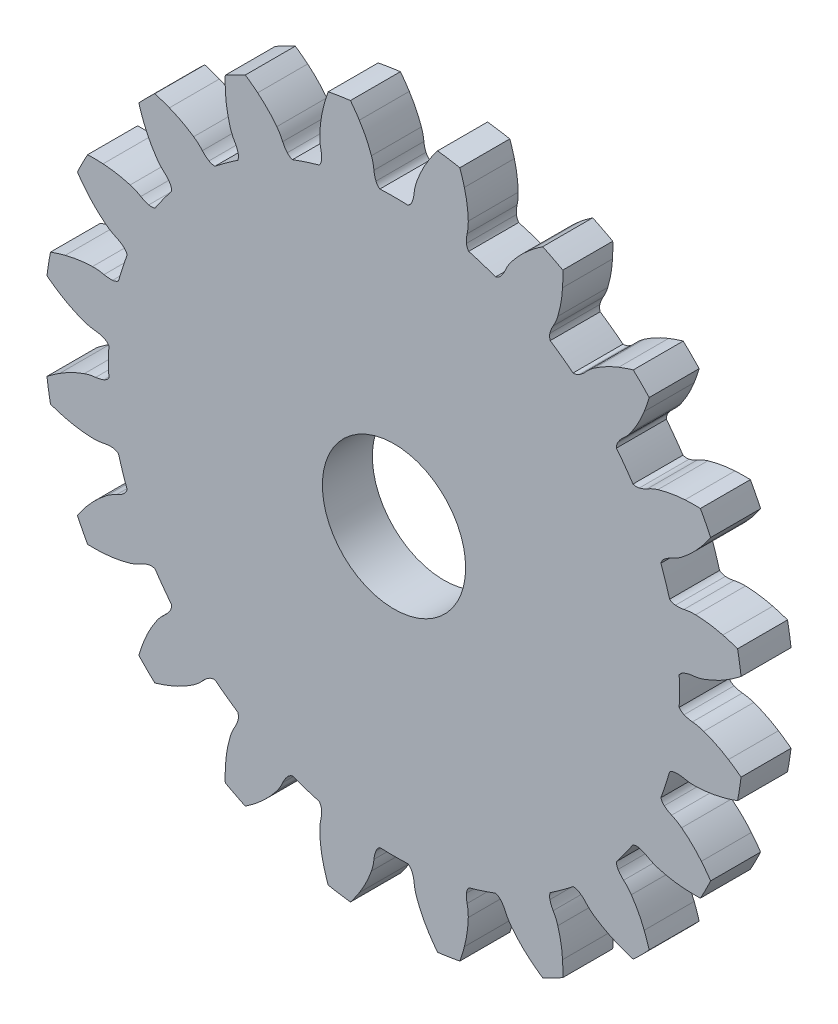
SolidWorks part; units mm, degrees
ref_plane "Front Plane" through (0, 0, 0) normal (0, 0, 1) x (1, 0, 0)
ref_plane "Top Plane" through (0, 0, 0) normal (0, 1, 0) x (1, 0, 0)
ref_plane "Right Plane" through (0, 0, 0) normal (1, 0, 0) x (0, 0, -1)
sketch "Model" plane through (0, 0, 0) normal (0, 0, 1) x (1, 0, 0)
  line L0 (-1.9599, -122.157) -> (1.9099, -120.8335)
  line L1 (1.9099, -120.8335) -> (1.9099, -119.1665)
  line L2 (1.9099, -119.1665) -> (-1.9599, -117.843)
  line L3 (-1.9599, -117.843) -> (-1.9599, -116.157)
  line L4 (-1.9599, -116.157) -> (1.9099, -114.8335)
  line L5 (1.9099, -114.8335) -> (1.9099, -113.1665)
  line L6 (1.9099, -113.1665) -> (-1.9599, -111.843)
  line L7 (-1.9599, -111.843) -> (-1.9599, -110.157)
  line L8 (-1.9599, -110.157) -> (1.9099, -108.8335)
  line L9 (1.9099, -108.8335) -> (1.9099, -107.1665)
  line L10 (1.9099, -107.1665) -> (-1.9599, -105.843)
  line L11 (-1.9599, -105.843) -> (-1.9599, -104.157)
  line L12 (-1.9599, -104.157) -> (1.9099, -102.8335)
  line L13 (1.9099, -102.8335) -> (1.9099, -101.1665)
  line L14 (1.9099, -101.1665) -> (-1.9599, -99.843)
  line L15 (-1.9599, -99.843) -> (-1.9599, -98.157)
  line L16 (-1.9599, -98.157) -> (1.9099, -96.8335)
  line L17 (1.9099, -96.8335) -> (1.9099, -95.1665)
  line L18 (1.9099, -95.1665) -> (-1.9599, -93.843)
  line L19 (-1.9599, -93.843) -> (-1.9599, -92.157)
  line L20 (-1.9599, -92.157) -> (1.9099, -90.8335)
  line L21 (1.9099, -90.8335) -> (1.9099, -89.1665)
  line L22 (1.9099, -89.1665) -> (-1.9599, -87.843)
  line L23 (-1.9599, -87.843) -> (-1.9599, -86.157)
  line L24 (-1.9599, -86.157) -> (1.9099, -84.8335)
  line L25 (1.9099, -84.8335) -> (1.9099, -83.1665)
  line L26 (1.9099, -83.1665) -> (-1.9599, -81.843)
  line L27 (-1.9599, -81.843) -> (-1.9599, -80.157)
  line L28 (-1.9599, -80.157) -> (1.9099, -78.8335)
  line L29 (1.9099, -78.8335) -> (1.9099, -77.1665)
  line L30 (1.9099, -77.1665) -> (-1.9599, -75.843)
  line L31 (-1.9599, -75.843) -> (-1.9599, -74.157)
  line L32 (-1.9599, -74.157) -> (1.9099, -72.8335)
  line L33 (1.9099, -72.8335) -> (1.9099, -71.1665)
  line L34 (1.9099, -71.1665) -> (-1.9599, -69.843)
  line L35 (-1.9599, -69.843) -> (-1.9599, -68.157)
  line L36 (-1.9599, -68.157) -> (1.9099, -66.8335)
  line L37 (1.9099, -66.8335) -> (1.9099, -65.1665)
  line L38 (1.9099, -65.1665) -> (-1.9599, -63.843)
  line L39 (-1.9599, -63.843) -> (-1.9599, -62.157)
  line L40 (-1.9599, -62.157) -> (1.9099, -60.8335)
  line L41 (1.9099, -60.8335) -> (1.9099, -59.1665)
  line L42 (1.9099, -59.1665) -> (-1.9599, -57.843)
  line L43 (-1.9599, -57.843) -> (-1.9599, -56.157)
  line L44 (-1.9599, -56.157) -> (1.9099, -54.8335)
  line L45 (1.9099, -54.8335) -> (1.9099, -53.1665)
  line L46 (1.9099, -53.1665) -> (-1.9599, -51.843)
  line L47 (-1.9599, -51.843) -> (-1.9599, -50.157)
  line L48 (-1.9599, -50.157) -> (1.9099, -48.8335)
  line L49 (1.9099, -48.8335) -> (1.9099, -47.1665)
  line L50 (1.9099, -47.1665) -> (-1.9599, -45.843)
  line L51 (-1.9599, -45.843) -> (-1.9599, -44.157)
  line L52 (-1.9599, -44.157) -> (1.9099, -42.8335)
  line L53 (1.9099, -42.8335) -> (1.9099, -41.1665)
  line L54 (1.9099, -41.1665) -> (-1.9599, -39.843)
  line L55 (-1.9599, -39.843) -> (-1.9599, -38.157)
  line L56 (-1.9599, -38.157) -> (1.9099, -36.8335)
  line L57 (1.9099, -36.8335) -> (1.9099, -35.1665)
  line L58 (1.9099, -35.1665) -> (-1.9599, -33.843)
  line L59 (-1.9599, -33.843) -> (-1.9599, -32.157)
  line L60 (-1.9599, -32.157) -> (1.9099, -30.8335)
  line L61 (1.9099, -30.8335) -> (1.9099, -29.1665)
  line L62 (1.9099, -29.1665) -> (-1.9599, -27.843)
  line L63 (-1.9599, -27.843) -> (-1.9599, -26.157)
  line L64 (-1.9599, -26.157) -> (1.9099, -24.8335)
  line L65 (1.9099, -24.8335) -> (1.9099, -23.1665)
  line L66 (1.9099, -23.1665) -> (-1.9599, -21.843)
  line L67 (-1.9599, -21.843) -> (-1.9599, -20.157)
  line L68 (-1.9599, -20.157) -> (1.9099, -18.8335)
  line L69 (1.9099, -18.8335) -> (1.9099, -17.1665)
  line L70 (1.9099, -17.1665) -> (-1.9599, -15.843)
  line L71 (-1.9599, -15.843) -> (-1.9599, -14.157)
  line L72 (-1.9599, -14.157) -> (1.9099, -12.8335)
  line L73 (1.9099, -12.8335) -> (1.9099, -11.1665)
  line L74 (1.9099, -11.1665) -> (-1.9599, -9.843)
  line L75 (-1.9599, -9.843) -> (-1.9599, -8.157)
  line L76 (-1.9599, -8.157) -> (1.9099, -6.8335)
  line L77 (1.9099, -6.8335) -> (1.9099, -5.1665)
  line L78 (1.9099, -5.1665) -> (-1.9599, -3.843)
  line L79 (-1.9599, -3.843) -> (-1.9599, -2.157)
  line L80 (-1.9599, -2.157) -> (1.9099, -0.8335)
  line L81 (1.9099, -0.8335) -> (1.9099, 0.8335)
  line L82 (1.9099, 0.8335) -> (-1.9599, 2.157)
  line L83 (-1.9599, 2.157) -> (-1.9599, 3.843)
  line L84 (-1.9599, 3.843) -> (1.9099, 5.1665)
  line L85 (1.9099, 5.1665) -> (1.9099, 6.8335)
  line L86 (1.9099, 6.8335) -> (-1.9599, 8.157)
  line L87 (-1.9599, 8.157) -> (-1.9599, 9.843)
  line L88 (-1.9599, 9.843) -> (1.9099, 11.1665)
  line L89 (1.9099, 11.1665) -> (1.9099, 12.8335)
  line L90 (1.9099, 12.8335) -> (-1.9599, 14.157)
  line L91 (-1.9599, 14.157) -> (-1.9599, 15.843)
  line L92 (-1.9599, 15.843) -> (1.9099, 17.1665)
  line L93 (1.9099, 17.1665) -> (1.9099, 18.8335)
  line L94 (1.9099, 18.8335) -> (-1.9599, 20.157)
  line L95 (-1.9599, 20.157) -> (-1.9599, 21.843)
  line L96 (-1.9599, 21.843) -> (1.9099, 23.1665)
  line L97 (1.9099, 23.1665) -> (1.9099, 24.8335)
  line L98 (1.9099, 24.8335) -> (-1.9599, 26.157)
  line L99 (-1.9599, 26.157) -> (-1.9599, 27.843)
  line L100 (-1.9599, 27.843) -> (1.9099, 29.1665)
  line L101 (1.9099, 29.1665) -> (1.9099, 30.8335)
  line L102 (1.9099, 30.8335) -> (-1.9599, 32.157)
  line L103 (-1.9599, 32.157) -> (-1.9599, 33.843)
  line L104 (-1.9599, 33.843) -> (1.9099, 35.1665)
  line L105 (1.9099, 35.1665) -> (1.9099, 36.8335)
  line L106 (1.9099, 36.8335) -> (-1.9599, 38.157)
  line L107 (-1.9599, 38.157) -> (-1.9599, 39.843)
  line L108 (-1.9599, 39.843) -> (1.9099, 41.1665)
  line L109 (1.9099, 41.1665) -> (1.9099, 42.8335)
  line L110 (1.9099, 42.8335) -> (-1.9599, 44.157)
  line L111 (-1.9599, 44.157) -> (-1.9599, 45.843)
  line L112 (-1.9599, 45.843) -> (1.9099, 47.1665)
  line L113 (1.9099, 47.1665) -> (1.9099, 48.8335)
  line L114 (1.9099, 48.8335) -> (-1.9599, 50.157)
  line L115 (-1.9599, 50.157) -> (-1.9599, 51.843)
  line L116 (-1.9599, 51.843) -> (1.9099, 53.1665)
  line L117 (1.9099, 53.1665) -> (1.9099, 54.8335)
  line L118 (1.9099, 54.8335) -> (-1.9599, 56.157)
  line L119 (-1.9599, 56.157) -> (-1.9599, 57.843)
  line L120 (-1.9599, 57.843) -> (1.9099, 59.1665)
  line L121 (1.9099, 59.1665) -> (1.9099, 60.8335)
  line L122 (1.9099, 60.8335) -> (-1.9599, 62.157)
  line L123 (-1.9599, 62.157) -> (-1.9599, 63.843)
  line L124 (-1.9599, 63.843) -> (1.9099, 65.1665)
  line L125 (1.9099, 65.1665) -> (1.9099, 66.8335)
  line L126 (1.9099, 66.8335) -> (-1.9599, 68.157)
  line L127 (-1.9599, 68.157) -> (-1.9599, 69.843)
  line L128 (-1.9599, 69.843) -> (1.9099, 71.1665)
  line L129 (1.9099, 71.1665) -> (1.9099, 72.8335)
  line L130 (1.9099, 72.8335) -> (-1.9599, 74.157)
  line L131 (-1.9599, 74.157) -> (-1.9599, 75.843)
  line L132 (-1.9599, 75.843) -> (1.9099, 77.1665)
  line L133 (1.9099, 77.1665) -> (1.9099, 78.8335)
  line L134 (1.9099, 78.8335) -> (-1.9599, 80.157)
  line L135 (-1.9599, 80.157) -> (-1.9599, 81.843)
  line L136 (-1.9599, 81.843) -> (1.9099, 83.1665)
  line L137 (1.9099, 83.1665) -> (1.9099, 84.8335)
  line L138 (1.9099, 84.8335) -> (-1.9599, 86.157)
  line L139 (-1.9599, 86.157) -> (-1.9599, 87.843)
  line L140 (-1.9599, 87.843) -> (1.9099, 89.1665)
  line L141 (1.9099, 89.1665) -> (1.9099, 90.8335)
  line L142 (1.9099, 90.8335) -> (-1.9599, 92.157)
  line L143 (-1.9599, 92.157) -> (-1.9599, 93.843)
  line L144 (-1.9599, 93.843) -> (1.9099, 95.1665)
  line L145 (1.9099, 95.1665) -> (1.9099, 96.8335)
  line L146 (1.9099, 96.8335) -> (-1.9599, 98.157)
  line L147 (-1.9599, 98.157) -> (-1.9599, 99.843)
  line L148 (-1.9599, 99.843) -> (1.9099, 101.1665)
  line L149 (1.9099, 101.1665) -> (1.9099, 102.8335)
  line L150 (1.9099, 102.8335) -> (-1.9599, 104.157)
  line L151 (-1.9599, 104.157) -> (-1.9599, 105.843)
  line L152 (-1.9599, 105.843) -> (1.9099, 107.1665)
  line L153 (1.9099, 107.1665) -> (1.9099, 108.8335)
  line L154 (1.9099, 108.8335) -> (-1.9599, 110.157)
  line L155 (-1.9599, 110.157) -> (-1.9599, 111.843)
  line L156 (-1.9599, 111.843) -> (1.9099, 113.1665)
  line L157 (1.9099, 113.1665) -> (1.9099, 114.8335)
  line L158 (1.9099, 114.8335) -> (-1.9599, 116.157)
  line L159 (-1.9599, 116.157) -> (-1.9599, 117.843)
  line L160 (-1.9599, 117.843) -> (1.9099, 119.1665)
  line L161 (1.9099, 119.1665) -> (1.9099, 120.8335)
  line L162 (1.9099, 120.8335) -> (-1.9599, 122.157)
  line L163 (-1.9599, 122.157) -> (-1.9599, 123)
  line L164 (-1.9599, 123) -> (-9.5993, 123)
  line L165 (-9.5993, 123) -> (-9.5993, -123)
  line L166 (-9.5993, -123) -> (-1.9599, -123)
  line L167 (-1.9599, -123) -> (-1.9599, -122.157)
  line L168 (-1.5377, 3.9366) -> (-1.6512, 3.2864)
  line L169 (-1.6512, 3.2864) -> (-1.7442, 2.6331)
  line L170 (-1.7442, 2.6331) -> (-1.7455, 2.6215)
  line L171 (-1.7455, 2.6215) -> (-1.7388, 2.6161)
  line L172 (-1.7388, 2.6161) -> (-1.4771, 2.4198)
  line L173 (-1.4771, 2.4198) -> (-1.2239, 2.242)
  line L174 (-1.2239, 2.242) -> (-0.9803, 2.082)
  line L175 (-0.9803, 2.082) -> (-0.7469, 1.9391)
  line L176 (-0.7469, 1.9391) -> (-0.5246, 1.8124)
  line L177 (-0.5246, 1.8124) -> (-0.3143, 1.7011)
  line L178 (-0.3143, 1.7011) -> (-0.1165, 1.6044)
  line L179 (-0.1165, 1.6044) -> (0.0679, 1.5212)
  line L180 (0.0679, 1.5212) -> (0.2383, 1.4506)
  line L181 (0.2383, 1.4506) -> (0.3942, 1.3918)
  line L182 (0.3942, 1.3918) -> (0.535, 1.3436)
  line L183 (0.535, 1.3436) -> (0.6602, 1.3051)
  line L184 (0.6602, 1.3051) -> (0.7694, 1.2753)
  line L185 (0.7694, 1.2753) -> (0.862, 1.2531)
  line L186 (0.862, 1.2531) -> (0.9379, 1.2374)
  line L187 (0.9379, 1.2374) -> (0.9966, 1.2272)
  line L188 (0.9966, 1.2272) -> (1.038, 1.2213)
  line L189 (1.038, 1.2213) -> (1.0618, 1.2187)
  line L190 (1.0618, 1.2187) -> (1.0916, 1.2164)
  line L191 (1.0916, 1.2164) -> (1.2696, 1.1958)
  line L192 (1.2696, 1.1958) -> (1.4284, 1.1659)
  line L193 (1.4284, 1.1659) -> (1.5676, 1.1277)
  line L194 (1.5676, 1.1277) -> (1.6869, 1.0826)
  line L195 (1.6869, 1.0826) -> (1.7859, 1.0316)
  line L196 (1.7859, 1.0316) -> (1.8646, 0.9761)
  line L197 (1.8646, 0.9761) -> (1.9226, 0.9172)
  line L198 (1.9226, 0.9172) -> (1.9599, 0.8563)
  line L199 (1.9599, 0.8563) -> (1.9764, 0.7945)
  line L200 (1.9764, 0.7945) -> (1.9599, 0.2692)
  line L201 (1.9599, 0.2692) -> (1.9599, -0.2692)
  line L202 (1.9599, -0.2692) -> (1.9764, -0.7945)
  line L203 (1.9764, -0.7945) -> (1.9599, -0.8563)
  line L204 (1.9599, -0.8563) -> (1.9226, -0.9172)
  line L205 (1.9226, -0.9172) -> (1.8646, -0.9761)
  line L206 (1.8646, -0.9761) -> (1.7859, -1.0316)
  line L207 (1.7859, -1.0316) -> (1.6869, -1.0826)
  line L208 (1.6869, -1.0826) -> (1.5676, -1.1277)
  line L209 (1.5676, -1.1277) -> (1.4284, -1.1659)
  line L210 (1.4284, -1.1659) -> (1.2696, -1.1958)
  line L211 (1.2696, -1.1958) -> (1.0916, -1.2164)
  line L212 (1.0916, -1.2164) -> (1.0618, -1.2187)
  line L213 (1.0618, -1.2187) -> (1.038, -1.2213)
  line L214 (1.038, -1.2213) -> (0.9966, -1.2272)
  line L215 (0.9966, -1.2272) -> (0.9379, -1.2374)
  line L216 (0.9379, -1.2374) -> (0.862, -1.2531)
  line L217 (0.862, -1.2531) -> (0.7694, -1.2753)
  line L218 (0.7694, -1.2753) -> (0.6602, -1.3051)
  line L219 (0.6602, -1.3051) -> (0.535, -1.3436)
  line L220 (0.535, -1.3436) -> (0.3942, -1.3918)
  line L221 (0.3942, -1.3918) -> (0.2383, -1.4506)
  line L222 (0.2383, -1.4506) -> (0.0679, -1.5212)
  line L223 (0.0679, -1.5212) -> (-0.1165, -1.6044)
  line L224 (-0.1165, -1.6044) -> (-0.3143, -1.7011)
  line L225 (-0.3143, -1.7011) -> (-0.5246, -1.8124)
  line L226 (-0.5246, -1.8124) -> (-0.7469, -1.9391)
  line L227 (-0.7469, -1.9391) -> (-0.9803, -2.082)
  line L228 (-0.9803, -2.082) -> (-1.2239, -2.242)
  line L229 (-1.2239, -2.242) -> (-1.4771, -2.4198)
  line L230 (-1.4771, -2.4198) -> (-1.7388, -2.6161)
  line L231 (-1.7388, -2.6161) -> (-1.7455, -2.6215)
  line L232 (-1.7455, -2.6215) -> (-1.7442, -2.6331)
  line L233 (-1.7442, -2.6331) -> (-1.6512, -3.2864)
  line L234 (-1.6512, -3.2864) -> (-1.5377, -3.9366)
  line L235 (-1.5377, -3.9366) -> (-1.5354, -3.948)
  line L236 (-1.5354, -3.948) -> (-1.5274, -3.951)
  line L237 (-1.5274, -3.951) -> (-1.2178, -4.0569)
  line L238 (-1.2178, -4.0569) -> (-0.9221, -4.1477)
  line L239 (-0.9221, -4.1477) -> (-0.6409, -4.2246)
  line L240 (-0.6409, -4.2246) -> (-0.3748, -4.2884)
  line L241 (-0.3748, -4.2884) -> (-0.1243, -4.3402)
  line L242 (-0.1243, -4.3402) -> (0.1102, -4.381)
  line L243 (0.1102, -4.381) -> (0.3281, -4.412)
  line L244 (0.3281, -4.412) -> (0.5292, -4.4341)
  line L245 (0.5292, -4.4341) -> (0.7132, -4.4485)
  line L246 (0.7132, -4.4485) -> (0.8796, -4.4563)
  line L247 (0.8796, -4.4563) -> (1.0284, -4.4586)
  line L248 (1.0284, -4.4586) -> (1.1593, -4.4565)
  line L249 (1.1593, -4.4565) -> (1.2724, -4.4511)
  line L250 (1.2724, -4.4511) -> (1.3673, -4.4436)
  line L251 (1.3673, -4.4436) -> (1.4443, -4.4351)
  line L252 (1.4443, -4.4351) -> (1.5034, -4.4267)
  line L253 (1.5034, -4.4267) -> (1.5445, -4.4195)
  line L254 (1.5445, -4.4195) -> (1.568, -4.4146)
  line L255 (1.568, -4.4146) -> (1.5971, -4.4076)
  line L256 (1.5971, -4.4076) -> (1.7727, -4.3722)
  line L257 (1.7727, -4.3722) -> (1.933, -4.3516)
  line L258 (1.933, -4.3516) -> (2.0771, -4.3448)
  line L259 (2.0771, -4.3448) -> (2.2045, -4.3509)
  line L260 (2.2045, -4.3509) -> (2.3145, -4.3688)
  line L261 (2.3145, -4.3688) -> (2.4064, -4.3973)
  line L262 (2.4064, -4.3973) -> (2.4798, -4.4353)
  line L263 (2.4798, -4.4353) -> (2.5341, -4.4818)
  line L264 (2.5341, -4.4818) -> (2.5689, -4.5354)
  line L265 (2.5689, -4.5354) -> (2.7155, -5.0401)
  line L266 (2.7155, -5.0401) -> (2.8819, -5.5522)
  line L267 (2.8819, -5.5522) -> (3.0599, -6.0467)
  line L268 (3.0599, -6.0467) -> (3.0633, -6.1105)
  line L269 (3.0633, -6.1105) -> (3.0467, -6.18)
  line L270 (3.0467, -6.18) -> (3.0097, -6.2539)
  line L271 (3.0097, -6.2539) -> (2.9521, -6.331)
  line L272 (2.9521, -6.331) -> (2.8736, -6.4101)
  line L273 (2.8736, -6.4101) -> (2.7741, -6.4899)
  line L274 (2.7741, -6.4899) -> (2.6535, -6.5692)
  line L275 (2.6535, -6.5692) -> (2.5118, -6.6468)
  line L276 (2.5118, -6.6468) -> (2.3488, -6.7213)
  line L277 (2.3488, -6.7213) -> (2.3212, -6.7327)
  line L278 (2.3212, -6.7327) -> (2.2993, -6.7426)
  line L279 (2.2993, -6.7426) -> (2.2618, -6.761)
  line L280 (2.2618, -6.761) -> (2.2091, -6.7888)
  line L281 (2.2091, -6.7888) -> (2.1418, -6.8272)
  line L282 (2.1418, -6.8272) -> (2.0605, -6.877)
  line L283 (2.0605, -6.877) -> (1.966, -6.939)
  line L284 (1.966, -6.939) -> (1.8588, -7.0143)
  line L285 (1.8588, -7.0143) -> (1.7398, -7.1036)
  line L286 (1.7398, -7.1036) -> (1.6097, -7.2078)
  line L287 (1.6097, -7.2078) -> (1.4694, -7.3275)
  line L288 (1.4694, -7.3275) -> (1.3197, -7.4636)
  line L289 (1.3197, -7.4636) -> (1.1616, -7.6168)
  line L290 (1.1616, -7.6168) -> (0.9959, -7.7876)
  line L291 (0.9959, -7.7876) -> (0.8236, -7.9768)
  line L292 (0.8236, -7.9768) -> (0.6459, -8.1848)
  line L293 (0.6459, -8.1848) -> (0.4635, -8.4123)
  line L294 (0.4635, -8.4123) -> (0.2777, -8.6596)
  line L295 (0.2777, -8.6596) -> (0.0895, -8.9272)
  line L296 (0.0895, -8.9272) -> (0.0848, -8.9344)
  line L297 (0.0848, -8.9344) -> (0.0896, -8.945)
  line L298 (0.0896, -8.945) -> (0.3799, -9.5376)
  line L299 (0.3799, -9.5376) -> (0.6887, -10.1209)
  line L300 (0.6887, -10.1209) -> (0.6945, -10.131)
  line L301 (0.6945, -10.131) -> (0.7031, -10.1314)
  line L302 (0.7031, -10.1314) -> (1.0302, -10.1364)
  line L303 (1.0302, -10.1364) -> (1.3395, -10.1315)
  line L304 (1.3395, -10.1315) -> (1.6307, -10.1177)
  line L305 (1.6307, -10.1177) -> (1.9035, -10.0961)
  line L306 (1.9035, -10.0961) -> (2.1578, -10.0679)
  line L307 (2.1578, -10.0679) -> (2.3934, -10.0343)
  line L308 (2.3934, -10.0343) -> (2.6102, -9.9964)
  line L309 (2.6102, -9.9964) -> (2.8083, -9.9553)
  line L310 (2.8083, -9.9553) -> (2.9877, -9.9122)
  line L311 (2.9877, -9.9122) -> (3.1484, -9.8682)
  line L312 (3.1484, -9.8682) -> (3.2906, -9.8244)
  line L313 (3.2906, -9.8244) -> (3.4145, -9.7819)
  line L314 (3.4145, -9.7819) -> (3.5203, -9.7419)
  line L315 (3.5203, -9.7419) -> (3.6083, -9.7054)
  line L316 (3.6083, -9.7054) -> (3.6789, -9.6735)
  line L317 (3.6789, -9.6735) -> (3.7324, -9.6473)
  line L318 (3.7324, -9.6473) -> (3.7694, -9.6277)
  line L319 (3.7694, -9.6277) -> (3.7902, -9.6158)
  line L320 (3.7902, -9.6158) -> (3.8157, -9.6002)
  line L321 (3.8157, -9.6002) -> (3.9718, -9.5122)
  line L322 (3.9718, -9.5122) -> (4.1178, -9.4431)
  line L323 (4.1178, -9.4431) -> (4.2529, -9.3921)
  line L324 (4.2529, -9.3921) -> (4.3759, -9.3585)
  line L325 (4.3759, -9.3585) -> (4.486, -9.3415)
  line L326 (4.486, -9.3415) -> (4.5822, -9.3402)
  line L327 (4.5822, -9.3402) -> (4.6638, -9.3538)
  line L328 (4.6638, -9.3538) -> (4.7297, -9.3811)
  line L329 (4.7297, -9.3811) -> (4.7794, -9.4214)
  line L330 (4.7794, -9.4214) -> (5.0748, -9.8561)
  line L331 (5.0748, -9.8561) -> (5.3913, -10.2917)
  line L332 (5.3913, -10.2917) -> (5.7134, -10.707)
  line L333 (5.7134, -10.707) -> (5.7364, -10.7667)
  line L334 (5.7364, -10.7667) -> (5.742, -10.8379)
  line L335 (5.742, -10.8379) -> (5.7297, -10.9196)
  line L336 (5.7297, -10.9196) -> (5.6987, -11.0107)
  line L337 (5.6987, -11.0107) -> (5.6485, -11.1102)
  line L338 (5.6485, -11.1102) -> (5.5786, -11.2168)
  line L339 (5.5786, -11.2168) -> (5.4884, -11.3295)
  line L340 (5.4884, -11.3295) -> (5.3775, -11.447)
  line L341 (5.3775, -11.447) -> (5.2456, -11.5683)
  line L342 (5.2456, -11.5683) -> (5.2228, -11.5877)
  line L343 (5.2228, -11.5877) -> (5.2051, -11.6038)
  line L344 (5.2051, -11.6038) -> (5.1751, -11.6329)
  line L345 (5.1751, -11.6329) -> (5.1336, -11.6757)
  line L346 (5.1336, -11.6757) -> (5.0815, -11.733)
  line L347 (5.0815, -11.733) -> (5.0195, -11.8054)
  line L348 (5.0195, -11.8054) -> (4.9488, -11.8937)
  line L349 (4.9488, -11.8937) -> (4.8701, -11.9984)
  line L350 (4.8701, -11.9984) -> (4.7845, -12.1201)
  line L351 (4.7845, -12.1201) -> (4.693, -12.2594)
  line L352 (4.693, -12.2594) -> (4.5965, -12.4166)
  line L353 (4.5965, -12.4166) -> (4.4962, -12.5923)
  line L354 (4.4962, -12.5923) -> (4.3932, -12.7868)
  line L355 (4.3932, -12.7868) -> (4.2884, -13.0005)
  line L356 (4.2884, -13.0005) -> (4.1831, -13.2337)
  line L357 (4.1831, -13.2337) -> (4.0782, -13.4865)
  line L358 (4.0782, -13.4865) -> (3.9751, -13.7591)
  line L359 (3.9751, -13.7591) -> (3.8748, -14.0517)
  line L360 (3.8748, -14.0517) -> (3.7785, -14.3644)
  line L361 (3.7785, -14.3644) -> (3.7763, -14.3727)
  line L362 (3.7763, -14.3727) -> (3.7841, -14.3813)
  line L363 (3.7841, -14.3813) -> (4.2434, -14.8552)
  line L364 (4.2434, -14.8552) -> (4.7173, -15.3145)
  line L365 (4.7173, -15.3145) -> (4.7259, -15.3223)
  line L366 (4.7259, -15.3223) -> (4.7342, -15.3201)
  line L367 (4.7342, -15.3201) -> (5.0469, -15.2238)
  line L368 (5.0469, -15.2238) -> (5.3395, -15.1235)
  line L369 (5.3395, -15.1235) -> (5.6121, -15.0203)
  line L370 (5.6121, -15.0203) -> (5.8649, -14.9155)
  line L371 (5.8649, -14.9155) -> (6.0981, -14.8102)
  line L372 (6.0981, -14.8102) -> (6.3117, -14.7054)
  line L373 (6.3117, -14.7054) -> (6.5063, -14.6023)
  line L374 (6.5063, -14.6023) -> (6.682, -14.5021)
  line L375 (6.682, -14.5021) -> (6.8392, -14.4056)
  line L376 (6.8392, -14.4056) -> (6.9785, -14.3141)
  line L377 (6.9785, -14.3141) -> (7.1002, -14.2285)
  line L378 (7.1002, -14.2285) -> (7.2049, -14.1498)
  line L379 (7.2049, -14.1498) -> (7.2932, -14.0791)
  line L380 (7.2932, -14.0791) -> (7.3656, -14.0171)
  line L381 (7.3656, -14.0171) -> (7.4229, -13.965)
  line L382 (7.4229, -13.965) -> (7.4657, -13.9235)
  line L383 (7.4657, -13.9235) -> (7.4948, -13.8935)
  line L384 (7.4948, -13.8935) -> (7.5109, -13.8758)
  line L385 (7.5109, -13.8758) -> (7.5303, -13.853)
  line L386 (7.5303, -13.853) -> (7.6515, -13.7211)
  line L387 (7.6515, -13.7211) -> (7.7691, -13.6102)
  line L388 (7.7691, -13.6102) -> (7.8818, -13.52)
  line L389 (7.8818, -13.52) -> (7.9884, -13.4501)
  line L390 (7.9884, -13.4501) -> (8.0879, -13.3999)
  line L391 (8.0879, -13.3999) -> (8.179, -13.3689)
  line L392 (8.179, -13.3689) -> (8.2607, -13.3566)
  line L393 (8.2607, -13.3566) -> (8.3319, -13.3622)
  line L394 (8.3319, -13.3622) -> (8.3916, -13.3852)
  line L395 (8.3916, -13.3852) -> (8.8069, -13.7073)
  line L396 (8.8069, -13.7073) -> (9.2425, -14.0238)
  line L397 (9.2425, -14.0238) -> (9.6772, -14.3192)
  line L398 (9.6772, -14.3192) -> (9.7175, -14.3688)
  line L399 (9.7175, -14.3688) -> (9.7448, -14.4348)
  line L400 (9.7448, -14.4348) -> (9.7584, -14.5164)
  line L401 (9.7584, -14.5164) -> (9.7571, -14.6126)
  line L402 (9.7571, -14.6126) -> (9.7401, -14.7227)
  line L403 (9.7401, -14.7227) -> (9.7065, -14.8457)
  line L404 (9.7065, -14.8457) -> (9.6555, -14.9808)
  line L405 (9.6555, -14.9808) -> (9.5864, -15.1268)
  line L406 (9.5864, -15.1268) -> (9.4984, -15.2829)
  line L407 (9.4984, -15.2829) -> (9.4828, -15.3084)
  line L408 (9.4828, -15.3084) -> (9.4709, -15.3292)
  line L409 (9.4709, -15.3292) -> (9.4513, -15.3661)
  line L410 (9.4513, -15.3661) -> (9.4251, -15.4197)
  line L411 (9.4251, -15.4197) -> (9.3932, -15.4903)
  line L412 (9.3932, -15.4903) -> (9.3567, -15.5783)
  line L413 (9.3567, -15.5783) -> (9.3167, -15.6841)
  line L414 (9.3167, -15.6841) -> (9.2742, -15.808)
  line L415 (9.2742, -15.808) -> (9.2304, -15.9502)
  line L416 (9.2304, -15.9502) -> (9.1864, -16.1109)
  line L417 (9.1864, -16.1109) -> (9.1433, -16.2903)
  line L418 (9.1433, -16.2903) -> (9.1022, -16.4884)
  line L419 (9.1022, -16.4884) -> (9.0643, -16.7052)
  line L420 (9.0643, -16.7052) -> (9.0307, -16.9408)
  line L421 (9.0307, -16.9408) -> (9.0025, -17.1951)
  line L422 (9.0025, -17.1951) -> (8.9809, -17.4679)
  line L423 (8.9809, -17.4679) -> (8.9671, -17.7591)
  line L424 (8.9671, -17.7591) -> (8.9622, -18.0684)
  line L425 (8.9622, -18.0684) -> (8.9672, -18.3955)
  line L426 (8.9672, -18.3955) -> (8.9676, -18.4041)
  line L427 (8.9676, -18.4041) -> (8.9777, -18.4098)
  line L428 (8.9777, -18.4098) -> (9.561, -18.7187)
  line L429 (9.561, -18.7187) -> (10.1536, -19.009)
  line L430 (10.1536, -19.009) -> (10.1642, -19.0138)
  line L431 (10.1642, -19.0138) -> (10.1714, -19.0091)
  line L432 (10.1714, -19.0091) -> (10.439, -18.8209)
  line L433 (10.439, -18.8209) -> (10.6863, -18.6351)
  line L434 (10.6863, -18.6351) -> (10.9138, -18.4527)
  line L435 (10.9138, -18.4527) -> (11.1218, -18.2749)
  line L436 (11.1218, -18.2749) -> (11.311, -18.1027)
  line L437 (11.311, -18.1027) -> (11.4818, -17.937)
  line L438 (11.4818, -17.937) -> (11.635, -17.7789)
  line L439 (11.635, -17.7789) -> (11.7711, -17.6292)
  line L440 (11.7711, -17.6292) -> (11.8908, -17.4889)
  line L441 (11.8908, -17.4889) -> (11.995, -17.3588)
  line L442 (11.995, -17.3588) -> (12.0843, -17.2398)
  line L443 (12.0843, -17.2398) -> (12.1596, -17.1326)
  line L444 (12.1596, -17.1326) -> (12.2216, -17.038)
  line L445 (12.2216, -17.038) -> (12.2714, -16.9568)
  line L446 (12.2714, -16.9568) -> (12.3098, -16.8895)
  line L447 (12.3098, -16.8895) -> (12.3376, -16.8368)
  line L448 (12.3376, -16.8368) -> (12.356, -16.7993)
  line L449 (12.356, -16.7993) -> (12.3659, -16.7774)
  line L450 (12.3659, -16.7774) -> (12.3773, -16.7498)
  line L451 (12.3773, -16.7498) -> (12.4518, -16.5868)
  line L452 (12.4518, -16.5868) -> (12.5294, -16.4451)
  line L453 (12.5294, -16.4451) -> (12.6087, -16.3245)
  line L454 (12.6087, -16.3245) -> (12.6885, -16.225)
  line L455 (12.6885, -16.225) -> (12.7676, -16.1465)
  line L456 (12.7676, -16.1465) -> (12.8447, -16.0889)
  line L457 (12.8447, -16.0889) -> (12.9186, -16.0519)
  line L458 (12.9186, -16.0519) -> (12.9881, -16.0353)
  line L459 (12.9881, -16.0353) -> (13.0519, -16.0387)
  line L460 (13.0519, -16.0387) -> (13.5464, -16.2167)
  line L461 (13.5464, -16.2167) -> (14.0585, -16.3831)
  line L462 (14.0585, -16.3831) -> (14.5632, -16.5297)
  line L463 (14.5632, -16.5297) -> (14.6168, -16.5645)
  line L464 (14.6168, -16.5645) -> (14.6633, -16.6188)
  line L465 (14.6633, -16.6188) -> (14.7013, -16.6922)
  line L466 (14.7013, -16.6922) -> (14.7298, -16.7841)
  line L467 (14.7298, -16.7841) -> (14.7477, -16.8941)
  line L468 (14.7477, -16.8941) -> (14.7538, -17.0214)
  line L469 (14.7538, -17.0214) -> (14.747, -17.1656)
  line L470 (14.747, -17.1656) -> (14.7264, -17.3259)
  line L471 (14.7264, -17.3259) -> (14.691, -17.5015)
  line L472 (14.691, -17.5015) -> (14.684, -17.5306)
  line L473 (14.684, -17.5306) -> (14.6791, -17.5541)
  line L474 (14.6791, -17.5541) -> (14.6719, -17.5952)
  line L475 (14.6719, -17.5952) -> (14.6635, -17.6543)
  line L476 (14.6635, -17.6543) -> (14.655, -17.7312)
  line L477 (14.655, -17.7312) -> (14.6475, -17.8262)
  line L478 (14.6475, -17.8262) -> (14.6421, -17.9392)
  line L479 (14.6421, -17.9392) -> (14.64, -18.0702)
  line L480 (14.64, -18.0702) -> (14.6423, -18.219)
  line L481 (14.6423, -18.219) -> (14.6501, -18.3854)
  line L482 (14.6501, -18.3854) -> (14.6645, -18.5693)
  line L483 (14.6645, -18.5693) -> (14.6866, -18.7704)
  line L484 (14.6866, -18.7704) -> (14.7176, -18.9884)
  line L485 (14.7176, -18.9884) -> (14.7584, -19.2229)
  line L486 (14.7584, -19.2229) -> (14.8102, -19.4734)
  line L487 (14.8102, -19.4734) -> (14.874, -19.7395)
  line L488 (14.874, -19.7395) -> (14.9508, -20.0207)
  line L489 (14.9508, -20.0207) -> (15.0417, -20.3164)
  line L490 (15.0417, -20.3164) -> (15.1476, -20.6259)
  line L491 (15.1476, -20.6259) -> (15.1506, -20.634)
  line L492 (15.1506, -20.634) -> (15.162, -20.6363)
  line L493 (15.162, -20.6363) -> (15.8121, -20.7498)
  line L494 (15.8121, -20.7498) -> (16.4655, -20.8428)
  line L495 (16.4655, -20.8428) -> (16.4771, -20.8441)
  line L496 (16.4771, -20.8441) -> (16.4825, -20.8374)
  line L497 (16.4825, -20.8374) -> (16.6788, -20.5757)
  line L498 (16.6788, -20.5757) -> (16.8566, -20.3225)
  line L499 (16.8566, -20.3225) -> (17.0166, -20.0789)
  line L500 (17.0166, -20.0789) -> (17.1595, -19.8455)
  line L501 (17.1595, -19.8455) -> (17.2862, -19.6232)
  line L502 (17.2862, -19.6232) -> (17.3974, -19.4129)
  line L503 (17.3974, -19.4129) -> (17.4942, -19.2151)
  line L504 (17.4942, -19.2151) -> (17.5774, -19.0307)
  line L505 (17.5774, -19.0307) -> (17.648, -18.8603)
  line L506 (17.648, -18.8603) -> (17.7068, -18.7044)
  line L507 (17.7068, -18.7044) -> (17.755, -18.5636)
  line L508 (17.755, -18.5636) -> (17.7935, -18.4384)
  line L509 (17.7935, -18.4384) -> (17.8233, -18.3292)
  line L510 (17.8233, -18.3292) -> (17.8455, -18.2366)
  line L511 (17.8455, -18.2366) -> (17.8612, -18.1607)
  line L512 (17.8612, -18.1607) -> (17.8714, -18.102)
  line L513 (17.8714, -18.102) -> (17.8773, -18.0606)
  line L514 (17.8773, -18.0606) -> (17.8799, -18.0368)
  line L515 (17.8799, -18.0368) -> (17.8822, -18.007)
  line L516 (17.8822, -18.007) -> (17.9028, -17.829)
  line L517 (17.9028, -17.829) -> (17.9327, -17.6702)
  line L518 (17.9327, -17.6702) -> (17.9709, -17.531)
  line L519 (17.9709, -17.531) -> (18.016, -17.4117)
  line L520 (18.016, -17.4117) -> (18.067, -17.3127)
  line L521 (18.067, -17.3127) -> (18.1225, -17.234)
  line L522 (18.1225, -17.234) -> (18.1814, -17.176)
  line L523 (18.1814, -17.176) -> (18.2423, -17.1387)
  line L524 (18.2423, -17.1387) -> (18.3041, -17.1222)
  line L525 (18.3041, -17.1222) -> (18.8294, -17.1387)
  line L526 (18.8294, -17.1387) -> (19.3678, -17.1387)
  line L527 (19.3678, -17.1387) -> (19.8931, -17.1222)
  line L528 (19.8931, -17.1222) -> (19.9549, -17.1387)
  line L529 (19.9549, -17.1387) -> (20.0158, -17.176)
  line L530 (20.0158, -17.176) -> (20.0747, -17.234)
  line L531 (20.0747, -17.234) -> (20.1302, -17.3127)
  line L532 (20.1302, -17.3127) -> (20.1812, -17.4117)
  line L533 (20.1812, -17.4117) -> (20.2263, -17.531)
  line L534 (20.2263, -17.531) -> (20.2645, -17.6702)
  line L535 (20.2645, -17.6702) -> (20.2944, -17.829)
  line L536 (20.2944, -17.829) -> (20.315, -18.007)
  line L537 (20.315, -18.007) -> (20.3173, -18.0368)
  line L538 (20.3173, -18.0368) -> (20.3199, -18.0606)
  line L539 (20.3199, -18.0606) -> (20.3258, -18.102)
  line L540 (20.3258, -18.102) -> (20.336, -18.1607)
  line L541 (20.336, -18.1607) -> (20.3517, -18.2366)
  line L542 (20.3517, -18.2366) -> (20.3739, -18.3292)
  line L543 (20.3739, -18.3292) -> (20.4037, -18.4384)
  line L544 (20.4037, -18.4384) -> (20.4422, -18.5636)
  line L545 (20.4422, -18.5636) -> (20.4904, -18.7044)
  line L546 (20.4904, -18.7044) -> (20.5492, -18.8603)
  line L547 (20.5492, -18.8603) -> (20.6198, -19.0307)
  line L548 (20.6198, -19.0307) -> (20.703, -19.2151)
  line L549 (20.703, -19.2151) -> (20.7997, -19.4129)
  line L550 (20.7997, -19.4129) -> (20.911, -19.6232)
  line L551 (20.911, -19.6232) -> (21.0377, -19.8455)
  line L552 (21.0377, -19.8455) -> (21.1806, -20.0789)
  line L553 (21.1806, -20.0789) -> (21.3406, -20.3225)
  line L554 (21.3406, -20.3225) -> (21.5184, -20.5757)
  line L555 (21.5184, -20.5757) -> (21.7147, -20.8374)
  line L556 (21.7147, -20.8374) -> (21.7201, -20.8441)
  line L557 (21.7201, -20.8441) -> (21.7317, -20.8428)
  line L558 (21.7317, -20.8428) -> (22.385, -20.7498)
  line L559 (22.385, -20.7498) -> (23.0352, -20.6363)
  line L560 (23.0352, -20.6363) -> (23.0466, -20.634)
  line L561 (23.0466, -20.634) -> (23.0496, -20.6259)
  line L562 (23.0496, -20.6259) -> (23.1555, -20.3164)
  line L563 (23.1555, -20.3164) -> (23.2463, -20.0207)
  line L564 (23.2463, -20.0207) -> (23.3232, -19.7395)
  line L565 (23.3232, -19.7395) -> (23.387, -19.4734)
  line L566 (23.387, -19.4734) -> (23.4388, -19.2229)
  line L567 (23.4388, -19.2229) -> (23.4796, -18.9884)
  line L568 (23.4796, -18.9884) -> (23.5106, -18.7704)
  line L569 (23.5106, -18.7704) -> (23.5327, -18.5693)
  line L570 (23.5327, -18.5693) -> (23.5471, -18.3854)
  line L571 (23.5471, -18.3854) -> (23.5549, -18.219)
  line L572 (23.5549, -18.219) -> (23.5572, -18.0702)
  line L573 (23.5572, -18.0702) -> (23.5551, -17.9392)
  line L574 (23.5551, -17.9392) -> (23.5497, -17.8262)
  line L575 (23.5497, -17.8262) -> (23.5422, -17.7312)
  line L576 (23.5422, -17.7312) -> (23.5337, -17.6543)
  line L577 (23.5337, -17.6543) -> (23.5253, -17.5952)
  line L578 (23.5253, -17.5952) -> (23.5181, -17.5541)
  line L579 (23.5181, -17.5541) -> (23.5132, -17.5306)
  line L580 (23.5132, -17.5306) -> (23.5062, -17.5015)
  line L581 (23.5062, -17.5015) -> (23.4708, -17.3259)
  line L582 (23.4708, -17.3259) -> (23.4502, -17.1656)
  line L583 (23.4502, -17.1656) -> (23.4434, -17.0214)
  line L584 (23.4434, -17.0214) -> (23.4495, -16.8941)
  line L585 (23.4495, -16.8941) -> (23.4674, -16.7841)
  line L586 (23.4674, -16.7841) -> (23.4959, -16.6922)
  line L587 (23.4959, -16.6922) -> (23.5339, -16.6188)
  line L588 (23.5339, -16.6188) -> (23.5804, -16.5645)
  line L589 (23.5804, -16.5645) -> (23.634, -16.5297)
  line L590 (23.634, -16.5297) -> (24.1387, -16.3831)
  line L591 (24.1387, -16.3831) -> (24.6508, -16.2167)
  line L592 (24.6508, -16.2167) -> (25.1453, -16.0387)
  line L593 (25.1453, -16.0387) -> (25.2091, -16.0353)
  line L594 (25.2091, -16.0353) -> (25.2786, -16.0519)
  line L595 (25.2786, -16.0519) -> (25.3525, -16.0889)
  line L596 (25.3525, -16.0889) -> (25.4296, -16.1465)
  line L597 (25.4296, -16.1465) -> (25.5087, -16.225)
  line L598 (25.5087, -16.225) -> (25.5885, -16.3245)
  line L599 (25.5885, -16.3245) -> (25.6678, -16.4451)
  line L600 (25.6678, -16.4451) -> (25.7453, -16.5868)
  line L601 (25.7453, -16.5868) -> (25.8199, -16.7498)
  line L602 (25.8199, -16.7498) -> (25.8313, -16.7774)
  line L603 (25.8313, -16.7774) -> (25.8412, -16.7993)
  line L604 (25.8412, -16.7993) -> (25.8595, -16.8368)
  line L605 (25.8595, -16.8368) -> (25.8874, -16.8895)
  line L606 (25.8874, -16.8895) -> (25.9258, -16.9568)
  line L607 (25.9258, -16.9568) -> (25.9755, -17.038)
  line L608 (25.9755, -17.038) -> (26.0376, -17.1326)
  line L609 (26.0376, -17.1326) -> (26.1129, -17.2398)
  line L610 (26.1129, -17.2398) -> (26.2022, -17.3588)
  line L611 (26.2022, -17.3588) -> (26.3064, -17.4889)
  line L612 (26.3064, -17.4889) -> (26.4261, -17.6292)
  line L613 (26.4261, -17.6292) -> (26.5622, -17.7789)
  line L614 (26.5622, -17.7789) -> (26.7154, -17.937)
  line L615 (26.7154, -17.937) -> (26.8862, -18.1027)
  line L616 (26.8862, -18.1027) -> (27.0754, -18.2749)
  line L617 (27.0754, -18.2749) -> (27.2834, -18.4527)
  line L618 (27.2834, -18.4527) -> (27.5109, -18.6351)
  line L619 (27.5109, -18.6351) -> (27.7582, -18.8209)
  line L620 (27.7582, -18.8209) -> (28.0258, -19.0091)
  line L621 (28.0258, -19.0091) -> (28.033, -19.0138)
  line L622 (28.033, -19.0138) -> (28.0436, -19.009)
  line L623 (28.0436, -19.009) -> (28.6362, -18.7187)
  line L624 (28.6362, -18.7187) -> (29.2195, -18.4098)
  line L625 (29.2195, -18.4098) -> (29.2296, -18.4041)
  line L626 (29.2296, -18.4041) -> (29.23, -18.3955)
  line L627 (29.23, -18.3955) -> (29.235, -18.0684)
  line L628 (29.235, -18.0684) -> (29.2301, -17.7591)
  line L629 (29.2301, -17.7591) -> (29.2162, -17.4679)
  line L630 (29.2162, -17.4679) -> (29.1947, -17.1951)
  line L631 (29.1947, -17.1951) -> (29.1665, -16.9408)
  line L632 (29.1665, -16.9408) -> (29.1329, -16.7052)
  line L633 (29.1329, -16.7052) -> (29.095, -16.4884)
  line L634 (29.095, -16.4884) -> (29.0539, -16.2903)
  line L635 (29.0539, -16.2903) -> (29.0108, -16.1109)
  line L636 (29.0108, -16.1109) -> (28.9668, -15.9502)
  line L637 (28.9668, -15.9502) -> (28.923, -15.808)
  line L638 (28.923, -15.808) -> (28.8805, -15.6841)
  line L639 (28.8805, -15.6841) -> (28.8405, -15.5783)
  line L640 (28.8405, -15.5783) -> (28.804, -15.4903)
  line L641 (28.804, -15.4903) -> (28.7721, -15.4197)
  line L642 (28.7721, -15.4197) -> (28.7459, -15.3661)
  line L643 (28.7459, -15.3661) -> (28.7263, -15.3292)
  line L644 (28.7263, -15.3292) -> (28.7144, -15.3084)
  line L645 (28.7144, -15.3084) -> (28.6988, -15.2829)
  line L646 (28.6988, -15.2829) -> (28.6108, -15.1268)
  line L647 (28.6108, -15.1268) -> (28.5416, -14.9808)
  line L648 (28.5416, -14.9808) -> (28.4907, -14.8457)
  line L649 (28.4907, -14.8457) -> (28.4571, -14.7227)
  line L650 (28.4571, -14.7227) -> (28.4401, -14.6126)
  line L651 (28.4401, -14.6126) -> (28.4388, -14.5164)
  line L652 (28.4388, -14.5164) -> (28.4523, -14.4348)
  line L653 (28.4523, -14.4348) -> (28.4797, -14.3688)
  line L654 (28.4797, -14.3688) -> (28.52, -14.3192)
  line L655 (28.52, -14.3192) -> (28.9547, -14.0238)
  line L656 (28.9547, -14.0238) -> (29.3903, -13.7073)
  line L657 (29.3903, -13.7073) -> (29.8056, -13.3852)
  line L658 (29.8056, -13.3852) -> (29.8652, -13.3622)
  line L659 (29.8652, -13.3622) -> (29.9365, -13.3566)
  line L660 (29.9365, -13.3566) -> (30.0182, -13.3689)
  line L661 (30.0182, -13.3689) -> (30.1093, -13.3999)
  line L662 (30.1093, -13.3999) -> (30.2088, -13.4501)
  line L663 (30.2088, -13.4501) -> (30.3154, -13.52)
  line L664 (30.3154, -13.52) -> (30.4281, -13.6102)
  line L665 (30.4281, -13.6102) -> (30.5456, -13.7211)
  line L666 (30.5456, -13.7211) -> (30.6669, -13.853)
  line L667 (30.6669, -13.853) -> (30.6863, -13.8758)
  line L668 (30.6863, -13.8758) -> (30.7024, -13.8935)
  line L669 (30.7024, -13.8935) -> (30.7315, -13.9235)
  line L670 (30.7315, -13.9235) -> (30.7743, -13.965)
  line L671 (30.7743, -13.965) -> (30.8316, -14.0171)
  line L672 (30.8316, -14.0171) -> (30.904, -14.0791)
  line L673 (30.904, -14.0791) -> (30.9923, -14.1498)
  line L674 (30.9923, -14.1498) -> (31.097, -14.2285)
  line L675 (31.097, -14.2285) -> (31.2187, -14.3141)
  line L676 (31.2187, -14.3141) -> (31.3579, -14.4056)
  line L677 (31.3579, -14.4056) -> (31.5152, -14.5021)
  line L678 (31.5152, -14.5021) -> (31.6909, -14.6023)
  line L679 (31.6909, -14.6023) -> (31.8854, -14.7054)
  line L680 (31.8854, -14.7054) -> (32.0991, -14.8102)
  line L681 (32.0991, -14.8102) -> (32.3323, -14.9155)
  line L682 (32.3323, -14.9155) -> (32.585, -15.0203)
  line L683 (32.585, -15.0203) -> (32.8577, -15.1235)
  line L684 (32.8577, -15.1235) -> (33.1503, -15.2238)
  line L685 (33.1503, -15.2238) -> (33.463, -15.3201)
  line L686 (33.463, -15.3201) -> (33.4713, -15.3223)
  line L687 (33.4713, -15.3223) -> (33.4799, -15.3145)
  line L688 (33.4799, -15.3145) -> (33.9538, -14.8552)
  line L689 (33.9538, -14.8552) -> (34.4131, -14.3813)
  line L690 (34.4131, -14.3813) -> (34.4209, -14.3727)
  line L691 (34.4209, -14.3727) -> (34.4187, -14.3644)
  line L692 (34.4187, -14.3644) -> (34.3224, -14.0517)
  line L693 (34.3224, -14.0517) -> (34.2221, -13.7591)
  line L694 (34.2221, -13.7591) -> (34.1189, -13.4865)
  line L695 (34.1189, -13.4865) -> (34.0141, -13.2337)
  line L696 (34.0141, -13.2337) -> (33.9088, -13.0005)
  line L697 (33.9088, -13.0005) -> (33.804, -12.7868)
  line L698 (33.804, -12.7868) -> (33.7009, -12.5923)
  line L699 (33.7009, -12.5923) -> (33.6006, -12.4166)
  line L700 (33.6006, -12.4166) -> (33.5042, -12.2594)
  line L701 (33.5042, -12.2594) -> (33.4127, -12.1201)
  line L702 (33.4127, -12.1201) -> (33.3271, -11.9984)
  line L703 (33.3271, -11.9984) -> (33.2484, -11.8937)
  line L704 (33.2484, -11.8937) -> (33.1776, -11.8054)
  line L705 (33.1776, -11.8054) -> (33.1157, -11.733)
  line L706 (33.1157, -11.733) -> (33.0636, -11.6757)
  line L707 (33.0636, -11.6757) -> (33.0221, -11.6329)
  line L708 (33.0221, -11.6329) -> (32.9921, -11.6038)
  line L709 (32.9921, -11.6038) -> (32.9744, -11.5877)
  line L710 (32.9744, -11.5877) -> (32.9516, -11.5683)
  line L711 (32.9516, -11.5683) -> (32.8196, -11.447)
  line L712 (32.8196, -11.447) -> (32.7088, -11.3295)
  line L713 (32.7088, -11.3295) -> (32.6186, -11.2168)
  line L714 (32.6186, -11.2168) -> (32.5486, -11.1102)
  line L715 (32.5486, -11.1102) -> (32.4985, -11.0107)
  line L716 (32.4985, -11.0107) -> (32.4675, -10.9196)
  line L717 (32.4675, -10.9196) -> (32.4551, -10.8379)
  line L718 (32.4551, -10.8379) -> (32.4608, -10.7667)
  line L719 (32.4608, -10.7667) -> (32.4838, -10.707)
  line L720 (32.4838, -10.707) -> (32.8059, -10.2917)
  line L721 (32.8059, -10.2917) -> (33.1224, -9.8561)
  line L722 (33.1224, -9.8561) -> (33.4178, -9.4214)
  line L723 (33.4178, -9.4214) -> (33.4674, -9.3811)
  line L724 (33.4674, -9.3811) -> (33.5334, -9.3538)
  line L725 (33.5334, -9.3538) -> (33.6149, -9.3402)
  line L726 (33.6149, -9.3402) -> (33.7112, -9.3415)
  line L727 (33.7112, -9.3415) -> (33.8213, -9.3585)
  line L728 (33.8213, -9.3585) -> (33.9443, -9.3921)
  line L729 (33.9443, -9.3921) -> (34.0794, -9.4431)
  line L730 (34.0794, -9.4431) -> (34.2254, -9.5122)
  line L731 (34.2254, -9.5122) -> (34.3815, -9.6002)
  line L732 (34.3815, -9.6002) -> (34.407, -9.6158)
  line L733 (34.407, -9.6158) -> (34.4278, -9.6277)
  line L734 (34.4278, -9.6277) -> (34.4647, -9.6473)
  line L735 (34.4647, -9.6473) -> (34.5183, -9.6735)
  line L736 (34.5183, -9.6735) -> (34.5889, -9.7054)
  line L737 (34.5889, -9.7054) -> (34.6769, -9.7419)
  line L738 (34.6769, -9.7419) -> (34.7827, -9.7819)
  line L739 (34.7827, -9.7819) -> (34.9066, -9.8244)
  line L740 (34.9066, -9.8244) -> (35.0488, -9.8682)
  line L741 (35.0488, -9.8682) -> (35.2095, -9.9122)
  line L742 (35.2095, -9.9122) -> (35.3889, -9.9553)
  line L743 (35.3889, -9.9553) -> (35.587, -9.9964)
  line L744 (35.587, -9.9964) -> (35.8038, -10.0343)
  line L745 (35.8038, -10.0343) -> (36.0394, -10.0679)
  line L746 (36.0394, -10.0679) -> (36.2937, -10.0961)
  line L747 (36.2937, -10.0961) -> (36.5665, -10.1177)
  line L748 (36.5665, -10.1177) -> (36.8577, -10.1315)
  line L749 (36.8577, -10.1315) -> (37.167, -10.1364)
  line L750 (37.167, -10.1364) -> (37.4941, -10.1314)
  line L751 (37.4941, -10.1314) -> (37.5027, -10.131)
  line L752 (37.5027, -10.131) -> (37.5084, -10.1209)
  line L753 (37.5084, -10.1209) -> (37.8173, -9.5376)
  line L754 (37.8173, -9.5376) -> (38.1076, -8.945)
  line L755 (38.1076, -8.945) -> (38.1124, -8.9344)
  line L756 (38.1124, -8.9344) -> (38.1077, -8.9272)
  line L757 (38.1077, -8.9272) -> (37.9195, -8.6596)
  line L758 (37.9195, -8.6596) -> (37.7337, -8.4123)
  line L759 (37.7337, -8.4123) -> (37.5513, -8.1848)
  line L760 (37.5513, -8.1848) -> (37.3735, -7.9768)
  line L761 (37.3735, -7.9768) -> (37.2013, -7.7876)
  line L762 (37.2013, -7.7876) -> (37.0356, -7.6168)
  line L763 (37.0356, -7.6168) -> (36.8775, -7.4636)
  line L764 (36.8775, -7.4636) -> (36.7278, -7.3275)
  line L765 (36.7278, -7.3275) -> (36.5875, -7.2078)
  line L766 (36.5875, -7.2078) -> (36.4574, -7.1036)
  line L767 (36.4574, -7.1036) -> (36.3384, -7.0143)
  line L768 (36.3384, -7.0143) -> (36.2312, -6.939)
  line L769 (36.2312, -6.939) -> (36.1366, -6.877)
  line L770 (36.1366, -6.877) -> (36.0554, -6.8272)
  line L771 (36.0554, -6.8272) -> (35.9881, -6.7888)
  line L772 (35.9881, -6.7888) -> (35.9354, -6.761)
  line L773 (35.9354, -6.761) -> (35.8979, -6.7426)
  line L774 (35.8979, -6.7426) -> (35.876, -6.7327)
  line L775 (35.876, -6.7327) -> (35.8483, -6.7213)
  line L776 (35.8483, -6.7213) -> (35.6854, -6.6468)
  line L777 (35.6854, -6.6468) -> (35.5437, -6.5692)
  line L778 (35.5437, -6.5692) -> (35.4231, -6.4899)
  line L779 (35.4231, -6.4899) -> (35.3236, -6.4101)
  line L780 (35.3236, -6.4101) -> (35.2451, -6.331)
  line L781 (35.2451, -6.331) -> (35.1875, -6.2539)
  line L782 (35.1875, -6.2539) -> (35.1505, -6.18)
  line L783 (35.1505, -6.18) -> (35.1339, -6.1105)
  line L784 (35.1339, -6.1105) -> (35.1373, -6.0467)
  line L785 (35.1373, -6.0467) -> (35.3153, -5.5522)
  line L786 (35.3153, -5.5522) -> (35.4817, -5.0401)
  line L787 (35.4817, -5.0401) -> (35.6283, -4.5354)
  line L788 (35.6283, -4.5354) -> (35.6631, -4.4818)
  line L789 (35.6631, -4.4818) -> (35.7174, -4.4353)
  line L790 (35.7174, -4.4353) -> (35.7908, -4.3973)
  line L791 (35.7908, -4.3973) -> (35.8827, -4.3688)
  line L792 (35.8827, -4.3688) -> (35.9926, -4.3509)
  line L793 (35.9926, -4.3509) -> (36.12, -4.3448)
  line L794 (36.12, -4.3448) -> (36.2642, -4.3516)
  line L795 (36.2642, -4.3516) -> (36.4245, -4.3722)
  line L796 (36.4245, -4.3722) -> (36.6001, -4.4076)
  line L797 (36.6001, -4.4076) -> (36.6292, -4.4146)
  line L798 (36.6292, -4.4146) -> (36.6527, -4.4195)
  line L799 (36.6527, -4.4195) -> (36.6938, -4.4267)
  line L800 (36.6938, -4.4267) -> (36.7529, -4.4351)
  line L801 (36.7529, -4.4351) -> (36.8298, -4.4436)
  line L802 (36.8298, -4.4436) -> (36.9248, -4.4511)
  line L803 (36.9248, -4.4511) -> (37.0378, -4.4565)
  line L804 (37.0378, -4.4565) -> (37.1688, -4.4586)
  line L805 (37.1688, -4.4586) -> (37.3176, -4.4563)
  line L806 (37.3176, -4.4563) -> (37.484, -4.4485)
  line L807 (37.484, -4.4485) -> (37.6679, -4.4341)
  line L808 (37.6679, -4.4341) -> (37.869, -4.412)
  line L809 (37.869, -4.412) -> (38.087, -4.381)
  line L810 (38.087, -4.381) -> (38.3215, -4.3402)
  line L811 (38.3215, -4.3402) -> (38.572, -4.2884)
  line L812 (38.572, -4.2884) -> (38.8381, -4.2246)
  line L813 (38.8381, -4.2246) -> (39.1193, -4.1477)
  line L814 (39.1193, -4.1477) -> (39.415, -4.0569)
  line L815 (39.415, -4.0569) -> (39.7245, -3.951)
  line L816 (39.7245, -3.951) -> (39.7326, -3.948)
  line L817 (39.7326, -3.948) -> (39.7349, -3.9366)
  line L818 (39.7349, -3.9366) -> (39.8484, -3.2864)
  line L819 (39.8484, -3.2864) -> (39.9414, -2.6331)
  line L820 (39.9414, -2.6331) -> (39.9427, -2.6215)
  line L821 (39.9427, -2.6215) -> (39.936, -2.6161)
  line L822 (39.936, -2.6161) -> (39.6743, -2.4198)
  line L823 (39.6743, -2.4198) -> (39.4211, -2.242)
  line L824 (39.4211, -2.242) -> (39.1774, -2.082)
  line L825 (39.1774, -2.082) -> (38.9441, -1.9391)
  line L826 (38.9441, -1.9391) -> (38.7218, -1.8124)
  line L827 (38.7218, -1.8124) -> (38.5115, -1.7011)
  line L828 (38.5115, -1.7011) -> (38.3137, -1.6044)
  line L829 (38.3137, -1.6044) -> (38.1293, -1.5212)
  line L830 (38.1293, -1.5212) -> (37.9588, -1.4506)
  line L831 (37.9588, -1.4506) -> (37.8029, -1.3918)
  line L832 (37.8029, -1.3918) -> (37.6622, -1.3436)
  line L833 (37.6622, -1.3436) -> (37.537, -1.3051)
  line L834 (37.537, -1.3051) -> (37.4278, -1.2753)
  line L835 (37.4278, -1.2753) -> (37.3352, -1.2531)
  line L836 (37.3352, -1.2531) -> (37.2593, -1.2374)
  line L837 (37.2593, -1.2374) -> (37.2006, -1.2272)
  line L838 (37.2006, -1.2272) -> (37.1592, -1.2213)
  line L839 (37.1592, -1.2213) -> (37.1354, -1.2187)
  line L840 (37.1354, -1.2187) -> (37.1055, -1.2164)
  line L841 (37.1055, -1.2164) -> (36.9276, -1.1958)
  line L842 (36.9276, -1.1958) -> (36.7688, -1.1659)
  line L843 (36.7688, -1.1659) -> (36.6296, -1.1277)
  line L844 (36.6296, -1.1277) -> (36.5103, -1.0826)
  line L845 (36.5103, -1.0826) -> (36.4112, -1.0316)
  line L846 (36.4112, -1.0316) -> (36.3326, -0.9761)
  line L847 (36.3326, -0.9761) -> (36.2746, -0.9172)
  line L848 (36.2746, -0.9172) -> (36.2373, -0.8563)
  line L849 (36.2373, -0.8563) -> (36.2208, -0.7945)
  line L850 (36.2208, -0.7945) -> (36.2373, -0.2692)
  line L851 (36.2373, -0.2692) -> (36.2373, 0.2692)
  line L852 (36.2373, 0.2692) -> (36.2208, 0.7945)
  line L853 (36.2208, 0.7945) -> (36.2373, 0.8563)
  line L854 (36.2373, 0.8563) -> (36.2746, 0.9172)
  line L855 (36.2746, 0.9172) -> (36.3326, 0.9761)
  line L856 (36.3326, 0.9761) -> (36.4112, 1.0316)
  line L857 (36.4112, 1.0316) -> (36.5103, 1.0826)
  line L858 (36.5103, 1.0826) -> (36.6296, 1.1277)
  line L859 (36.6296, 1.1277) -> (36.7688, 1.1659)
  line L860 (36.7688, 1.1659) -> (36.9276, 1.1958)
  line L861 (36.9276, 1.1958) -> (37.1055, 1.2164)
  line L862 (37.1055, 1.2164) -> (37.1354, 1.2187)
  line L863 (37.1354, 1.2187) -> (37.1592, 1.2213)
  line L864 (37.1592, 1.2213) -> (37.2006, 1.2272)
  line L865 (37.2006, 1.2272) -> (37.2593, 1.2374)
  line L866 (37.2593, 1.2374) -> (37.3352, 1.2531)
  line L867 (37.3352, 1.2531) -> (37.4278, 1.2753)
  line L868 (37.4278, 1.2753) -> (37.537, 1.3051)
  line L869 (37.537, 1.3051) -> (37.6622, 1.3436)
  line L870 (37.6622, 1.3436) -> (37.8029, 1.3918)
  line L871 (37.8029, 1.3918) -> (37.9588, 1.4506)
  line L872 (37.9588, 1.4506) -> (38.1293, 1.5212)
  line L873 (38.1293, 1.5212) -> (38.3137, 1.6044)
  line L874 (38.3137, 1.6044) -> (38.5115, 1.7011)
  line L875 (38.5115, 1.7011) -> (38.7218, 1.8124)
  line L876 (38.7218, 1.8124) -> (38.9441, 1.9391)
  line L877 (38.9441, 1.9391) -> (39.1774, 2.082)
  line L878 (39.1774, 2.082) -> (39.4211, 2.242)
  line L879 (39.4211, 2.242) -> (39.6743, 2.4198)
  line L880 (39.6743, 2.4198) -> (39.936, 2.6161)
  line L881 (39.936, 2.6161) -> (39.9427, 2.6215)
  line L882 (39.9427, 2.6215) -> (39.9414, 2.6331)
  line L883 (39.9414, 2.6331) -> (39.8484, 3.2864)
  line L884 (39.8484, 3.2864) -> (39.7349, 3.9366)
  line L885 (39.7349, 3.9366) -> (39.7326, 3.948)
  line L886 (39.7326, 3.948) -> (39.7245, 3.951)
  line L887 (39.7245, 3.951) -> (39.415, 4.0569)
  line L888 (39.415, 4.0569) -> (39.1193, 4.1477)
  line L889 (39.1193, 4.1477) -> (38.8381, 4.2246)
  line L890 (38.8381, 4.2246) -> (38.572, 4.2884)
  line L891 (38.572, 4.2884) -> (38.3215, 4.3402)
  line L892 (38.3215, 4.3402) -> (38.087, 4.381)
  line L893 (38.087, 4.381) -> (37.869, 4.412)
  line L894 (37.869, 4.412) -> (37.6679, 4.4341)
  line L895 (37.6679, 4.4341) -> (37.484, 4.4485)
  line L896 (37.484, 4.4485) -> (37.3176, 4.4563)
  line L897 (37.3176, 4.4563) -> (37.1688, 4.4586)
  line L898 (37.1688, 4.4586) -> (37.0378, 4.4565)
  line L899 (37.0378, 4.4565) -> (36.9248, 4.4511)
  line L900 (36.9248, 4.4511) -> (36.8298, 4.4436)
  line L901 (36.8298, 4.4436) -> (36.7529, 4.4351)
  line L902 (36.7529, 4.4351) -> (36.6938, 4.4267)
  line L903 (36.6938, 4.4267) -> (36.6527, 4.4195)
  line L904 (36.6527, 4.4195) -> (36.6292, 4.4146)
  line L905 (36.6292, 4.4146) -> (36.6001, 4.4076)
  line L906 (36.6001, 4.4076) -> (36.4245, 4.3722)
  line L907 (36.4245, 4.3722) -> (36.2642, 4.3516)
  line L908 (36.2642, 4.3516) -> (36.12, 4.3448)
  line L909 (36.12, 4.3448) -> (35.9926, 4.3509)
  line L910 (35.9926, 4.3509) -> (35.8827, 4.3688)
  line L911 (35.8827, 4.3688) -> (35.7908, 4.3973)
  line L912 (35.7908, 4.3973) -> (35.7174, 4.4353)
  line L913 (35.7174, 4.4353) -> (35.6631, 4.4818)
  line L914 (35.6631, 4.4818) -> (35.6283, 4.5354)
  line L915 (35.6283, 4.5354) -> (35.4817, 5.0401)
  line L916 (35.4817, 5.0401) -> (35.3153, 5.5522)
  line L917 (35.3153, 5.5522) -> (35.1373, 6.0467)
  line L918 (35.1373, 6.0467) -> (35.1339, 6.1105)
  line L919 (35.1339, 6.1105) -> (35.1505, 6.18)
  line L920 (35.1505, 6.18) -> (35.1875, 6.2539)
  line L921 (35.1875, 6.2539) -> (35.2451, 6.331)
  line L922 (35.2451, 6.331) -> (35.3236, 6.4101)
  line L923 (35.3236, 6.4101) -> (35.4231, 6.4899)
  line L924 (35.4231, 6.4899) -> (35.5437, 6.5692)
  line L925 (35.5437, 6.5692) -> (35.6854, 6.6468)
  line L926 (35.6854, 6.6468) -> (35.8483, 6.7213)
  line L927 (35.8483, 6.7213) -> (35.876, 6.7327)
  line L928 (35.876, 6.7327) -> (35.8979, 6.7426)
  line L929 (35.8979, 6.7426) -> (35.9354, 6.761)
  line L930 (35.9354, 6.761) -> (35.9881, 6.7888)
  line L931 (35.9881, 6.7888) -> (36.0554, 6.8272)
  line L932 (36.0554, 6.8272) -> (36.1366, 6.877)
  line L933 (36.1366, 6.877) -> (36.2312, 6.939)
  line L934 (36.2312, 6.939) -> (36.3384, 7.0143)
  line L935 (36.3384, 7.0143) -> (36.4574, 7.1036)
  line L936 (36.4574, 7.1036) -> (36.5875, 7.2078)
  line L937 (36.5875, 7.2078) -> (36.7278, 7.3275)
  line L938 (36.7278, 7.3275) -> (36.8775, 7.4636)
  line L939 (36.8775, 7.4636) -> (37.0356, 7.6168)
  line L940 (37.0356, 7.6168) -> (37.2013, 7.7876)
  line L941 (37.2013, 7.7876) -> (37.3735, 7.9768)
  line L942 (37.3735, 7.9768) -> (37.5513, 8.1848)
  line L943 (37.5513, 8.1848) -> (37.7337, 8.4123)
  line L944 (37.7337, 8.4123) -> (37.9195, 8.6596)
  line L945 (37.9195, 8.6596) -> (38.1077, 8.9272)
  line L946 (38.1077, 8.9272) -> (38.1124, 8.9344)
  line L947 (38.1124, 8.9344) -> (38.1076, 8.945)
  line L948 (38.1076, 8.945) -> (37.8173, 9.5376)
  line L949 (37.8173, 9.5376) -> (37.5084, 10.1209)
  line L950 (37.5084, 10.1209) -> (37.5027, 10.131)
  line L951 (37.5027, 10.131) -> (37.4941, 10.1314)
  line L952 (37.4941, 10.1314) -> (37.167, 10.1364)
  line L953 (37.167, 10.1364) -> (36.8577, 10.1315)
  line L954 (36.8577, 10.1315) -> (36.5665, 10.1177)
  line L955 (36.5665, 10.1177) -> (36.2937, 10.0961)
  line L956 (36.2937, 10.0961) -> (36.0394, 10.0679)
  line L957 (36.0394, 10.0679) -> (35.8038, 10.0343)
  line L958 (35.8038, 10.0343) -> (35.587, 9.9964)
  line L959 (35.587, 9.9964) -> (35.3889, 9.9553)
  line L960 (35.3889, 9.9553) -> (35.2095, 9.9122)
  line L961 (35.2095, 9.9122) -> (35.0488, 9.8682)
  line L962 (35.0488, 9.8682) -> (34.9066, 9.8244)
  line L963 (34.9066, 9.8244) -> (34.7827, 9.7819)
  line L964 (34.7827, 9.7819) -> (34.6769, 9.7419)
  line L965 (34.6769, 9.7419) -> (34.5889, 9.7054)
  line L966 (34.5889, 9.7054) -> (34.5183, 9.6735)
  line L967 (34.5183, 9.6735) -> (34.4647, 9.6473)
  line L968 (34.4647, 9.6473) -> (34.4278, 9.6277)
  line L969 (34.4278, 9.6277) -> (34.407, 9.6158)
  line L970 (34.407, 9.6158) -> (34.3815, 9.6002)
  line L971 (34.3815, 9.6002) -> (34.2254, 9.5122)
  line L972 (34.2254, 9.5122) -> (34.0794, 9.4431)
  line L973 (34.0794, 9.4431) -> (33.9443, 9.3921)
  line L974 (33.9443, 9.3921) -> (33.8213, 9.3585)
  line L975 (33.8213, 9.3585) -> (33.7112, 9.3415)
  line L976 (33.7112, 9.3415) -> (33.6149, 9.3402)
  line L977 (33.6149, 9.3402) -> (33.5334, 9.3538)
  line L978 (33.5334, 9.3538) -> (33.4674, 9.3811)
  line L979 (33.4674, 9.3811) -> (33.4178, 9.4214)
  line L980 (33.4178, 9.4214) -> (33.1224, 9.8561)
  line L981 (33.1224, 9.8561) -> (32.8059, 10.2917)
  line L982 (32.8059, 10.2917) -> (32.4838, 10.707)
  line L983 (32.4838, 10.707) -> (32.4608, 10.7667)
  line L984 (32.4608, 10.7667) -> (32.4551, 10.8379)
  line L985 (32.4551, 10.8379) -> (32.4675, 10.9196)
  line L986 (32.4675, 10.9196) -> (32.4985, 11.0107)
  line L987 (32.4985, 11.0107) -> (32.5486, 11.1102)
  line L988 (32.5486, 11.1102) -> (32.6186, 11.2168)
  line L989 (32.6186, 11.2168) -> (32.7088, 11.3295)
  line L990 (32.7088, 11.3295) -> (32.8196, 11.447)
  line L991 (32.8196, 11.447) -> (32.9516, 11.5683)
  line L992 (32.9516, 11.5683) -> (32.9744, 11.5877)
  line L993 (32.9744, 11.5877) -> (32.9921, 11.6038)
  line L994 (32.9921, 11.6038) -> (33.0221, 11.6329)
  line L995 (33.0221, 11.6329) -> (33.0636, 11.6757)
  line L996 (33.0636, 11.6757) -> (33.1157, 11.733)
  line L997 (33.1157, 11.733) -> (33.1776, 11.8054)
  line L998 (33.1776, 11.8054) -> (33.2484, 11.8937)
  line L999 (33.2484, 11.8937) -> (33.3271, 11.9984)
  line L1000 (33.3271, 11.9984) -> (33.4127, 12.1201)
  line L1001 (33.4127, 12.1201) -> (33.5042, 12.2594)
  line L1002 (33.5042, 12.2594) -> (33.6006, 12.4166)
  line L1003 (33.6006, 12.4166) -> (33.7009, 12.5923)
  line L1004 (33.7009, 12.5923) -> (33.804, 12.7868)
  line L1005 (33.804, 12.7868) -> (33.9088, 13.0005)
  line L1006 (33.9088, 13.0005) -> (34.0141, 13.2337)
  line L1007 (34.0141, 13.2337) -> (34.1189, 13.4865)
  line L1008 (34.1189, 13.4865) -> (34.2221, 13.7591)
  line L1009 (34.2221, 13.7591) -> (34.3224, 14.0517)
  line L1010 (34.3224, 14.0517) -> (34.4187, 14.3644)
  line L1011 (34.4187, 14.3644) -> (34.4209, 14.3727)
  line L1012 (34.4209, 14.3727) -> (34.4131, 14.3813)
  line L1013 (34.4131, 14.3813) -> (33.9538, 14.8552)
  line L1014 (33.9538, 14.8552) -> (33.4799, 15.3145)
  line L1015 (33.4799, 15.3145) -> (33.4713, 15.3223)
  line L1016 (33.4713, 15.3223) -> (33.463, 15.3201)
  line L1017 (33.463, 15.3201) -> (33.1503, 15.2238)
  line L1018 (33.1503, 15.2238) -> (32.8577, 15.1235)
  line L1019 (32.8577, 15.1235) -> (32.585, 15.0203)
  line L1020 (32.585, 15.0203) -> (32.3323, 14.9155)
  line L1021 (32.3323, 14.9155) -> (32.0991, 14.8102)
  line L1022 (32.0991, 14.8102) -> (31.8854, 14.7054)
  line L1023 (31.8854, 14.7054) -> (31.6909, 14.6023)
  line L1024 (31.6909, 14.6023) -> (31.5152, 14.5021)
  line L1025 (31.5152, 14.5021) -> (31.3579, 14.4056)
  line L1026 (31.3579, 14.4056) -> (31.2187, 14.3141)
  line L1027 (31.2187, 14.3141) -> (31.097, 14.2285)
  line L1028 (31.097, 14.2285) -> (30.9923, 14.1498)
  line L1029 (30.9923, 14.1498) -> (30.904, 14.0791)
  line L1030 (30.904, 14.0791) -> (30.8316, 14.0171)
  line L1031 (30.8316, 14.0171) -> (30.7743, 13.965)
  line L1032 (30.7743, 13.965) -> (30.7315, 13.9235)
  line L1033 (30.7315, 13.9235) -> (30.7024, 13.8935)
  line L1034 (30.7024, 13.8935) -> (30.6863, 13.8758)
  line L1035 (30.6863, 13.8758) -> (30.6669, 13.853)
  line L1036 (30.6669, 13.853) -> (30.5456, 13.7211)
  line L1037 (30.5456, 13.7211) -> (30.4281, 13.6102)
  line L1038 (30.4281, 13.6102) -> (30.3154, 13.52)
  line L1039 (30.3154, 13.52) -> (30.2088, 13.4501)
  line L1040 (30.2088, 13.4501) -> (30.1093, 13.3999)
  line L1041 (30.1093, 13.3999) -> (30.0182, 13.3689)
  line L1042 (30.0182, 13.3689) -> (29.9365, 13.3566)
  line L1043 (29.9365, 13.3566) -> (29.8652, 13.3622)
  line L1044 (29.8652, 13.3622) -> (29.8056, 13.3852)
  line L1045 (29.8056, 13.3852) -> (29.3903, 13.7073)
  line L1046 (29.3903, 13.7073) -> (28.9547, 14.0238)
  line L1047 (28.9547, 14.0238) -> (28.52, 14.3192)
  line L1048 (28.52, 14.3192) -> (28.4797, 14.3688)
  line L1049 (28.4797, 14.3688) -> (28.4523, 14.4348)
  line L1050 (28.4523, 14.4348) -> (28.4388, 14.5164)
  line L1051 (28.4388, 14.5164) -> (28.4401, 14.6126)
  line L1052 (28.4401, 14.6126) -> (28.4571, 14.7227)
  line L1053 (28.4571, 14.7227) -> (28.4907, 14.8457)
  line L1054 (28.4907, 14.8457) -> (28.5416, 14.9808)
  line L1055 (28.5416, 14.9808) -> (28.6108, 15.1268)
  line L1056 (28.6108, 15.1268) -> (28.6988, 15.2829)
  line L1057 (28.6988, 15.2829) -> (28.7144, 15.3084)
  line L1058 (28.7144, 15.3084) -> (28.7263, 15.3292)
  line L1059 (28.7263, 15.3292) -> (28.7459, 15.3661)
  line L1060 (28.7459, 15.3661) -> (28.7721, 15.4197)
  line L1061 (28.7721, 15.4197) -> (28.804, 15.4903)
  line L1062 (28.804, 15.4903) -> (28.8405, 15.5783)
  line L1063 (28.8405, 15.5783) -> (28.8805, 15.6841)
  line L1064 (28.8805, 15.6841) -> (28.923, 15.808)
  line L1065 (28.923, 15.808) -> (28.9668, 15.9502)
  line L1066 (28.9668, 15.9502) -> (29.0108, 16.1109)
  line L1067 (29.0108, 16.1109) -> (29.0539, 16.2903)
  line L1068 (29.0539, 16.2903) -> (29.095, 16.4884)
  line L1069 (29.095, 16.4884) -> (29.1329, 16.7052)
  line L1070 (29.1329, 16.7052) -> (29.1665, 16.9408)
  line L1071 (29.1665, 16.9408) -> (29.1947, 17.1951)
  line L1072 (29.1947, 17.1951) -> (29.2162, 17.4679)
  line L1073 (29.2162, 17.4679) -> (29.2301, 17.7591)
  line L1074 (29.2301, 17.7591) -> (29.235, 18.0684)
  line L1075 (29.235, 18.0684) -> (29.23, 18.3955)
  line L1076 (29.23, 18.3955) -> (29.2296, 18.4041)
  line L1077 (29.2296, 18.4041) -> (29.2195, 18.4098)
  line L1078 (29.2195, 18.4098) -> (28.6362, 18.7187)
  line L1079 (28.6362, 18.7187) -> (28.0436, 19.009)
  line L1080 (28.0436, 19.009) -> (28.033, 19.0138)
  line L1081 (28.033, 19.0138) -> (28.0258, 19.0091)
  line L1082 (28.0258, 19.0091) -> (27.7582, 18.8209)
  line L1083 (27.7582, 18.8209) -> (27.5109, 18.6351)
  line L1084 (27.5109, 18.6351) -> (27.2834, 18.4527)
  line L1085 (27.2834, 18.4527) -> (27.0754, 18.2749)
  line L1086 (27.0754, 18.2749) -> (26.8862, 18.1027)
  line L1087 (26.8862, 18.1027) -> (26.7154, 17.937)
  line L1088 (26.7154, 17.937) -> (26.5622, 17.7789)
  line L1089 (26.5622, 17.7789) -> (26.4261, 17.6292)
  line L1090 (26.4261, 17.6292) -> (26.3064, 17.4889)
  line L1091 (26.3064, 17.4889) -> (26.2022, 17.3588)
  line L1092 (26.2022, 17.3588) -> (26.1129, 17.2398)
  line L1093 (26.1129, 17.2398) -> (26.0376, 17.1326)
  line L1094 (26.0376, 17.1326) -> (25.9755, 17.038)
  line L1095 (25.9755, 17.038) -> (25.9258, 16.9568)
  line L1096 (25.9258, 16.9568) -> (25.8874, 16.8895)
  line L1097 (25.8874, 16.8895) -> (25.8595, 16.8368)
  line L1098 (25.8595, 16.8368) -> (25.8412, 16.7993)
  line L1099 (25.8412, 16.7993) -> (25.8313, 16.7774)
  line L1100 (25.8313, 16.7774) -> (25.8199, 16.7498)
  line L1101 (25.8199, 16.7498) -> (25.7453, 16.5868)
  line L1102 (25.7453, 16.5868) -> (25.6678, 16.4451)
  line L1103 (25.6678, 16.4451) -> (25.5885, 16.3245)
  line L1104 (25.5885, 16.3245) -> (25.5087, 16.225)
  line L1105 (25.5087, 16.225) -> (25.4296, 16.1465)
  line L1106 (25.4296, 16.1465) -> (25.3525, 16.0889)
  line L1107 (25.3525, 16.0889) -> (25.2786, 16.0519)
  line L1108 (25.2786, 16.0519) -> (25.2091, 16.0353)
  line L1109 (25.2091, 16.0353) -> (25.1453, 16.0387)
  line L1110 (25.1453, 16.0387) -> (24.6508, 16.2167)
  line L1111 (24.6508, 16.2167) -> (24.1387, 16.3831)
  line L1112 (24.1387, 16.3831) -> (23.634, 16.5297)
  line L1113 (23.634, 16.5297) -> (23.5804, 16.5645)
  line L1114 (23.5804, 16.5645) -> (23.5339, 16.6188)
  line L1115 (23.5339, 16.6188) -> (23.4959, 16.6922)
  line L1116 (23.4959, 16.6922) -> (23.4674, 16.7841)
  line L1117 (23.4674, 16.7841) -> (23.4495, 16.8941)
  line L1118 (23.4495, 16.8941) -> (23.4434, 17.0214)
  line L1119 (23.4434, 17.0214) -> (23.4502, 17.1656)
  line L1120 (23.4502, 17.1656) -> (23.4708, 17.3259)
  line L1121 (23.4708, 17.3259) -> (23.5062, 17.5015)
  line L1122 (23.5062, 17.5015) -> (23.5132, 17.5306)
  line L1123 (23.5132, 17.5306) -> (23.5181, 17.5541)
  line L1124 (23.5181, 17.5541) -> (23.5253, 17.5952)
  line L1125 (23.5253, 17.5952) -> (23.5337, 17.6543)
  line L1126 (23.5337, 17.6543) -> (23.5422, 17.7312)
  line L1127 (23.5422, 17.7312) -> (23.5497, 17.8262)
  line L1128 (23.5497, 17.8262) -> (23.5551, 17.9392)
  line L1129 (23.5551, 17.9392) -> (23.5572, 18.0702)
  line L1130 (23.5572, 18.0702) -> (23.5549, 18.219)
  line L1131 (23.5549, 18.219) -> (23.5471, 18.3854)
  line L1132 (23.5471, 18.3854) -> (23.5327, 18.5693)
  line L1133 (23.5327, 18.5693) -> (23.5106, 18.7704)
  line L1134 (23.5106, 18.7704) -> (23.4796, 18.9884)
  line L1135 (23.4796, 18.9884) -> (23.4388, 19.2229)
  line L1136 (23.4388, 19.2229) -> (23.387, 19.4734)
  line L1137 (23.387, 19.4734) -> (23.3232, 19.7395)
  line L1138 (23.3232, 19.7395) -> (23.2463, 20.0207)
  line L1139 (23.2463, 20.0207) -> (23.1555, 20.3164)
  line L1140 (23.1555, 20.3164) -> (23.0496, 20.6259)
  line L1141 (23.0496, 20.6259) -> (23.0466, 20.634)
  line L1142 (23.0466, 20.634) -> (23.0352, 20.6363)
  line L1143 (23.0352, 20.6363) -> (22.385, 20.7498)
  line L1144 (22.385, 20.7498) -> (21.7317, 20.8428)
  line L1145 (21.7317, 20.8428) -> (21.7201, 20.8441)
  line L1146 (21.7201, 20.8441) -> (21.7147, 20.8374)
  line L1147 (21.7147, 20.8374) -> (21.5184, 20.5757)
  line L1148 (21.5184, 20.5757) -> (21.3406, 20.3225)
  line L1149 (21.3406, 20.3225) -> (21.1806, 20.0789)
  line L1150 (21.1806, 20.0789) -> (21.0377, 19.8455)
  line L1151 (21.0377, 19.8455) -> (20.911, 19.6232)
  line L1152 (20.911, 19.6232) -> (20.7997, 19.4129)
  line L1153 (20.7997, 19.4129) -> (20.703, 19.2151)
  line L1154 (20.703, 19.2151) -> (20.6198, 19.0307)
  line L1155 (20.6198, 19.0307) -> (20.5492, 18.8603)
  line L1156 (20.5492, 18.8603) -> (20.4904, 18.7044)
  line L1157 (20.4904, 18.7044) -> (20.4422, 18.5636)
  line L1158 (20.4422, 18.5636) -> (20.4037, 18.4384)
  line L1159 (20.4037, 18.4384) -> (20.3739, 18.3292)
  line L1160 (20.3739, 18.3292) -> (20.3517, 18.2366)
  line L1161 (20.3517, 18.2366) -> (20.336, 18.1607)
  line L1162 (20.336, 18.1607) -> (20.3258, 18.102)
  line L1163 (20.3258, 18.102) -> (20.3199, 18.0606)
  line L1164 (20.3199, 18.0606) -> (20.3173, 18.0368)
  line L1165 (20.3173, 18.0368) -> (20.315, 18.007)
  line L1166 (20.315, 18.007) -> (20.2944, 17.829)
  line L1167 (20.2944, 17.829) -> (20.2645, 17.6702)
  line L1168 (20.2645, 17.6702) -> (20.2263, 17.531)
  line L1169 (20.2263, 17.531) -> (20.1812, 17.4117)
  line L1170 (20.1812, 17.4117) -> (20.1302, 17.3127)
  line L1171 (20.1302, 17.3127) -> (20.0747, 17.234)
  line L1172 (20.0747, 17.234) -> (20.0158, 17.176)
  line L1173 (20.0158, 17.176) -> (19.9549, 17.1387)
  line L1174 (19.9549, 17.1387) -> (19.8931, 17.1222)
  line L1175 (19.8931, 17.1222) -> (19.3678, 17.1387)
  line L1176 (19.3678, 17.1387) -> (18.8294, 17.1387)
  line L1177 (18.8294, 17.1387) -> (18.3041, 17.1222)
  line L1178 (18.3041, 17.1222) -> (18.2423, 17.1387)
  line L1179 (18.2423, 17.1387) -> (18.1814, 17.176)
  line L1180 (18.1814, 17.176) -> (18.1225, 17.234)
  line L1181 (18.1225, 17.234) -> (18.067, 17.3127)
  line L1182 (18.067, 17.3127) -> (18.016, 17.4117)
  line L1183 (18.016, 17.4117) -> (17.9709, 17.531)
  line L1184 (17.9709, 17.531) -> (17.9327, 17.6702)
  line L1185 (17.9327, 17.6702) -> (17.9028, 17.829)
  line L1186 (17.9028, 17.829) -> (17.8822, 18.007)
  line L1187 (17.8822, 18.007) -> (17.8799, 18.0368)
  line L1188 (17.8799, 18.0368) -> (17.8773, 18.0606)
  line L1189 (17.8773, 18.0606) -> (17.8714, 18.102)
  line L1190 (17.8714, 18.102) -> (17.8612, 18.1607)
  line L1191 (17.8612, 18.1607) -> (17.8455, 18.2366)
  line L1192 (17.8455, 18.2366) -> (17.8233, 18.3292)
  line L1193 (17.8233, 18.3292) -> (17.7935, 18.4384)
  line L1194 (17.7935, 18.4384) -> (17.755, 18.5636)
  line L1195 (17.755, 18.5636) -> (17.7068, 18.7044)
  line L1196 (17.7068, 18.7044) -> (17.648, 18.8603)
  line L1197 (17.648, 18.8603) -> (17.5774, 19.0307)
  line L1198 (17.5774, 19.0307) -> (17.4942, 19.2151)
  line L1199 (17.4942, 19.2151) -> (17.3974, 19.4129)
  line L1200 (17.3974, 19.4129) -> (17.2862, 19.6232)
  line L1201 (17.2862, 19.6232) -> (17.1595, 19.8455)
  line L1202 (17.1595, 19.8455) -> (17.0166, 20.0789)
  line L1203 (17.0166, 20.0789) -> (16.8566, 20.3225)
  line L1204 (16.8566, 20.3225) -> (16.6788, 20.5757)
  line L1205 (16.6788, 20.5757) -> (16.4825, 20.8374)
  line L1206 (16.4825, 20.8374) -> (16.4771, 20.8441)
  line L1207 (16.4771, 20.8441) -> (16.4655, 20.8428)
  line L1208 (16.4655, 20.8428) -> (15.8121, 20.7498)
  line L1209 (15.8121, 20.7498) -> (15.162, 20.6363)
  line L1210 (15.162, 20.6363) -> (15.1506, 20.634)
  line L1211 (15.1506, 20.634) -> (15.1476, 20.6259)
  line L1212 (15.1476, 20.6259) -> (15.0417, 20.3164)
  line L1213 (15.0417, 20.3164) -> (14.9508, 20.0207)
  line L1214 (14.9508, 20.0207) -> (14.874, 19.7395)
  line L1215 (14.874, 19.7395) -> (14.8102, 19.4734)
  line L1216 (14.8102, 19.4734) -> (14.7584, 19.2229)
  line L1217 (14.7584, 19.2229) -> (14.7176, 18.9884)
  line L1218 (14.7176, 18.9884) -> (14.6866, 18.7704)
  line L1219 (14.6866, 18.7704) -> (14.6645, 18.5693)
  line L1220 (14.6645, 18.5693) -> (14.6501, 18.3854)
  line L1221 (14.6501, 18.3854) -> (14.6423, 18.219)
  line L1222 (14.6423, 18.219) -> (14.64, 18.0702)
  line L1223 (14.64, 18.0702) -> (14.6421, 17.9392)
  line L1224 (14.6421, 17.9392) -> (14.6475, 17.8262)
  line L1225 (14.6475, 17.8262) -> (14.655, 17.7312)
  line L1226 (14.655, 17.7312) -> (14.6635, 17.6543)
  line L1227 (14.6635, 17.6543) -> (14.6719, 17.5952)
  line L1228 (14.6719, 17.5952) -> (14.6791, 17.5541)
  line L1229 (14.6791, 17.5541) -> (14.684, 17.5306)
  line L1230 (14.684, 17.5306) -> (14.691, 17.5015)
  line L1231 (14.691, 17.5015) -> (14.7264, 17.3259)
  line L1232 (14.7264, 17.3259) -> (14.747, 17.1656)
  line L1233 (14.747, 17.1656) -> (14.7538, 17.0214)
  line L1234 (14.7538, 17.0214) -> (14.7477, 16.8941)
  line L1235 (14.7477, 16.8941) -> (14.7298, 16.7841)
  line L1236 (14.7298, 16.7841) -> (14.7013, 16.6922)
  line L1237 (14.7013, 16.6922) -> (14.6633, 16.6188)
  line L1238 (14.6633, 16.6188) -> (14.6168, 16.5645)
  line L1239 (14.6168, 16.5645) -> (14.5632, 16.5297)
  line L1240 (14.5632, 16.5297) -> (14.0585, 16.3831)
  line L1241 (14.0585, 16.3831) -> (13.5464, 16.2167)
  line L1242 (13.5464, 16.2167) -> (13.0519, 16.0387)
  line L1243 (13.0519, 16.0387) -> (12.9881, 16.0353)
  line L1244 (12.9881, 16.0353) -> (12.9186, 16.0519)
  line L1245 (12.9186, 16.0519) -> (12.8447, 16.0889)
  line L1246 (12.8447, 16.0889) -> (12.7676, 16.1465)
  line L1247 (12.7676, 16.1465) -> (12.6885, 16.225)
  line L1248 (12.6885, 16.225) -> (12.6087, 16.3245)
  line L1249 (12.6087, 16.3245) -> (12.5294, 16.4451)
  line L1250 (12.5294, 16.4451) -> (12.4518, 16.5868)
  line L1251 (12.4518, 16.5868) -> (12.3773, 16.7498)
  line L1252 (12.3773, 16.7498) -> (12.3659, 16.7774)
  line L1253 (12.3659, 16.7774) -> (12.356, 16.7993)
  line L1254 (12.356, 16.7993) -> (12.3376, 16.8368)
  line L1255 (12.3376, 16.8368) -> (12.3098, 16.8895)
  line L1256 (12.3098, 16.8895) -> (12.2714, 16.9568)
  line L1257 (12.2714, 16.9568) -> (12.2216, 17.038)
  line L1258 (12.2216, 17.038) -> (12.1596, 17.1326)
  line L1259 (12.1596, 17.1326) -> (12.0843, 17.2398)
  line L1260 (12.0843, 17.2398) -> (11.995, 17.3588)
  line L1261 (11.995, 17.3588) -> (11.8908, 17.4889)
  line L1262 (11.8908, 17.4889) -> (11.7711, 17.6292)
  line L1263 (11.7711, 17.6292) -> (11.635, 17.7789)
  line L1264 (11.635, 17.7789) -> (11.4818, 17.937)
  line L1265 (11.4818, 17.937) -> (11.311, 18.1027)
  line L1266 (11.311, 18.1027) -> (11.1218, 18.2749)
  line L1267 (11.1218, 18.2749) -> (10.9138, 18.4527)
  line L1268 (10.9138, 18.4527) -> (10.6863, 18.6351)
  line L1269 (10.6863, 18.6351) -> (10.439, 18.8209)
  line L1270 (10.439, 18.8209) -> (10.1714, 19.0091)
  line L1271 (10.1714, 19.0091) -> (10.1642, 19.0138)
  line L1272 (10.1642, 19.0138) -> (10.1536, 19.009)
  line L1273 (10.1536, 19.009) -> (9.561, 18.7187)
  line L1274 (9.561, 18.7187) -> (8.9777, 18.4098)
  line L1275 (8.9777, 18.4098) -> (8.9676, 18.4041)
  line L1276 (8.9676, 18.4041) -> (8.9672, 18.3955)
  line L1277 (8.9672, 18.3955) -> (8.9622, 18.0684)
  line L1278 (8.9622, 18.0684) -> (8.9671, 17.7591)
  line L1279 (8.9671, 17.7591) -> (8.9809, 17.4679)
  line L1280 (8.9809, 17.4679) -> (9.0025, 17.1951)
  line L1281 (9.0025, 17.1951) -> (9.0307, 16.9408)
  line L1282 (9.0307, 16.9408) -> (9.0643, 16.7052)
  line L1283 (9.0643, 16.7052) -> (9.1022, 16.4884)
  line L1284 (9.1022, 16.4884) -> (9.1433, 16.2903)
  line L1285 (9.1433, 16.2903) -> (9.1864, 16.1109)
  line L1286 (9.1864, 16.1109) -> (9.2304, 15.9502)
  line L1287 (9.2304, 15.9502) -> (9.2742, 15.808)
  line L1288 (9.2742, 15.808) -> (9.3167, 15.6841)
  line L1289 (9.3167, 15.6841) -> (9.3567, 15.5783)
  line L1290 (9.3567, 15.5783) -> (9.3932, 15.4903)
  line L1291 (9.3932, 15.4903) -> (9.4251, 15.4197)
  line L1292 (9.4251, 15.4197) -> (9.4513, 15.3661)
  line L1293 (9.4513, 15.3661) -> (9.4709, 15.3292)
  line L1294 (9.4709, 15.3292) -> (9.4828, 15.3084)
  line L1295 (9.4828, 15.3084) -> (9.4984, 15.2829)
  line L1296 (9.4984, 15.2829) -> (9.5864, 15.1268)
  line L1297 (9.5864, 15.1268) -> (9.6555, 14.9808)
  line L1298 (9.6555, 14.9808) -> (9.7065, 14.8457)
  line L1299 (9.7065, 14.8457) -> (9.7401, 14.7227)
  line L1300 (9.7401, 14.7227) -> (9.7571, 14.6126)
  line L1301 (9.7571, 14.6126) -> (9.7584, 14.5164)
  line L1302 (9.7584, 14.5164) -> (9.7448, 14.4348)
  line L1303 (9.7448, 14.4348) -> (9.7175, 14.3688)
  line L1304 (9.7175, 14.3688) -> (9.6772, 14.3192)
  line L1305 (9.6772, 14.3192) -> (9.2425, 14.0238)
  line L1306 (9.2425, 14.0238) -> (8.8069, 13.7073)
  line L1307 (8.8069, 13.7073) -> (8.3916, 13.3852)
  line L1308 (8.3916, 13.3852) -> (8.3319, 13.3622)
  line L1309 (8.3319, 13.3622) -> (8.2607, 13.3566)
  line L1310 (8.2607, 13.3566) -> (8.179, 13.3689)
  line L1311 (8.179, 13.3689) -> (8.0879, 13.3999)
  line L1312 (8.0879, 13.3999) -> (7.9884, 13.4501)
  line L1313 (7.9884, 13.4501) -> (7.8818, 13.52)
  line L1314 (7.8818, 13.52) -> (7.7691, 13.6102)
  line L1315 (7.7691, 13.6102) -> (7.6515, 13.7211)
  line L1316 (7.6515, 13.7211) -> (7.5303, 13.853)
  line L1317 (7.5303, 13.853) -> (7.5109, 13.8758)
  line L1318 (7.5109, 13.8758) -> (7.4948, 13.8935)
  line L1319 (7.4948, 13.8935) -> (7.4657, 13.9235)
  line L1320 (7.4657, 13.9235) -> (7.4229, 13.965)
  line L1321 (7.4229, 13.965) -> (7.3656, 14.0171)
  line L1322 (7.3656, 14.0171) -> (7.2932, 14.0791)
  line L1323 (7.2932, 14.0791) -> (7.2049, 14.1498)
  line L1324 (7.2049, 14.1498) -> (7.1002, 14.2285)
  line L1325 (7.1002, 14.2285) -> (6.9785, 14.3141)
  line L1326 (6.9785, 14.3141) -> (6.8392, 14.4056)
  line L1327 (6.8392, 14.4056) -> (6.682, 14.5021)
  line L1328 (6.682, 14.5021) -> (6.5063, 14.6023)
  line L1329 (6.5063, 14.6023) -> (6.3117, 14.7054)
  line L1330 (6.3117, 14.7054) -> (6.0981, 14.8102)
  line L1331 (6.0981, 14.8102) -> (5.8649, 14.9155)
  line L1332 (5.8649, 14.9155) -> (5.6121, 15.0203)
  line L1333 (5.6121, 15.0203) -> (5.3395, 15.1235)
  line L1334 (5.3395, 15.1235) -> (5.0469, 15.2238)
  line L1335 (5.0469, 15.2238) -> (4.7342, 15.3201)
  line L1336 (4.7342, 15.3201) -> (4.7259, 15.3223)
  line L1337 (4.7259, 15.3223) -> (4.7173, 15.3145)
  line L1338 (4.7173, 15.3145) -> (4.2434, 14.8552)
  line L1339 (4.2434, 14.8552) -> (3.7841, 14.3813)
  line L1340 (3.7841, 14.3813) -> (3.7763, 14.3727)
  line L1341 (3.7763, 14.3727) -> (3.7785, 14.3644)
  line L1342 (3.7785, 14.3644) -> (3.8748, 14.0517)
  line L1343 (3.8748, 14.0517) -> (3.9751, 13.7591)
  line L1344 (3.9751, 13.7591) -> (4.0782, 13.4865)
  line L1345 (4.0782, 13.4865) -> (4.1831, 13.2337)
  line L1346 (4.1831, 13.2337) -> (4.2884, 13.0005)
  line L1347 (4.2884, 13.0005) -> (4.3932, 12.7868)
  line L1348 (4.3932, 12.7868) -> (4.4962, 12.5923)
  line L1349 (4.4962, 12.5923) -> (4.5965, 12.4166)
  line L1350 (4.5965, 12.4166) -> (4.693, 12.2594)
  line L1351 (4.693, 12.2594) -> (4.7845, 12.1201)
  line L1352 (4.7845, 12.1201) -> (4.8701, 11.9984)
  line L1353 (4.8701, 11.9984) -> (4.9488, 11.8937)
  line L1354 (4.9488, 11.8937) -> (5.0195, 11.8054)
  line L1355 (5.0195, 11.8054) -> (5.0815, 11.733)
  line L1356 (5.0815, 11.733) -> (5.1336, 11.6757)
  line L1357 (5.1336, 11.6757) -> (5.1751, 11.6329)
  line L1358 (5.1751, 11.6329) -> (5.2051, 11.6038)
  line L1359 (5.2051, 11.6038) -> (5.2228, 11.5877)
  line L1360 (5.2228, 11.5877) -> (5.2456, 11.5683)
  line L1361 (5.2456, 11.5683) -> (5.3775, 11.447)
  line L1362 (5.3775, 11.447) -> (5.4884, 11.3295)
  line L1363 (5.4884, 11.3295) -> (5.5786, 11.2168)
  line L1364 (5.5786, 11.2168) -> (5.6485, 11.1102)
  line L1365 (5.6485, 11.1102) -> (5.6987, 11.0107)
  line L1366 (5.6987, 11.0107) -> (5.7297, 10.9196)
  line L1367 (5.7297, 10.9196) -> (5.742, 10.8379)
  line L1368 (5.742, 10.8379) -> (5.7364, 10.7667)
  line L1369 (5.7364, 10.7667) -> (5.7134, 10.707)
  line L1370 (5.7134, 10.707) -> (5.3913, 10.2917)
  line L1371 (5.3913, 10.2917) -> (5.0748, 9.8561)
  line L1372 (5.0748, 9.8561) -> (4.7794, 9.4214)
  line L1373 (4.7794, 9.4214) -> (4.7297, 9.3811)
  line L1374 (4.7297, 9.3811) -> (4.6638, 9.3538)
  line L1375 (4.6638, 9.3538) -> (4.5822, 9.3402)
  line L1376 (4.5822, 9.3402) -> (4.486, 9.3415)
  line L1377 (4.486, 9.3415) -> (4.3759, 9.3585)
  line L1378 (4.3759, 9.3585) -> (4.2529, 9.3921)
  line L1379 (4.2529, 9.3921) -> (4.1178, 9.4431)
  line L1380 (4.1178, 9.4431) -> (3.9718, 9.5122)
  line L1381 (3.9718, 9.5122) -> (3.8157, 9.6002)
  line L1382 (3.8157, 9.6002) -> (3.7902, 9.6158)
  line L1383 (3.7902, 9.6158) -> (3.7694, 9.6277)
  line L1384 (3.7694, 9.6277) -> (3.7324, 9.6473)
  line L1385 (3.7324, 9.6473) -> (3.6789, 9.6735)
  line L1386 (3.6789, 9.6735) -> (3.6083, 9.7054)
  line L1387 (3.6083, 9.7054) -> (3.5203, 9.7419)
  line L1388 (3.5203, 9.7419) -> (3.4145, 9.7819)
  line L1389 (3.4145, 9.7819) -> (3.2906, 9.8244)
  line L1390 (3.2906, 9.8244) -> (3.1484, 9.8682)
  line L1391 (3.1484, 9.8682) -> (2.9877, 9.9122)
  line L1392 (2.9877, 9.9122) -> (2.8083, 9.9553)
  line L1393 (2.8083, 9.9553) -> (2.6102, 9.9964)
  line L1394 (2.6102, 9.9964) -> (2.3934, 10.0343)
  line L1395 (2.3934, 10.0343) -> (2.1578, 10.0679)
  line L1396 (2.1578, 10.0679) -> (1.9035, 10.0961)
  line L1397 (1.9035, 10.0961) -> (1.6307, 10.1177)
  line L1398 (1.6307, 10.1177) -> (1.3395, 10.1315)
  line L1399 (1.3395, 10.1315) -> (1.0302, 10.1364)
  line L1400 (1.0302, 10.1364) -> (0.7031, 10.1314)
  line L1401 (0.7031, 10.1314) -> (0.6945, 10.131)
  line L1402 (0.6945, 10.131) -> (0.6887, 10.1209)
  line L1403 (0.6887, 10.1209) -> (0.3799, 9.5376)
  line L1404 (0.3799, 9.5376) -> (0.0896, 8.945)
  line L1405 (0.0896, 8.945) -> (0.0848, 8.9344)
  line L1406 (0.0848, 8.9344) -> (0.0895, 8.9272)
  line L1407 (0.0895, 8.9272) -> (0.2777, 8.6596)
  line L1408 (0.2777, 8.6596) -> (0.4635, 8.4123)
  line L1409 (0.4635, 8.4123) -> (0.6459, 8.1848)
  line L1410 (0.6459, 8.1848) -> (0.8236, 7.9768)
  line L1411 (0.8236, 7.9768) -> (0.9959, 7.7876)
  line L1412 (0.9959, 7.7876) -> (1.1616, 7.6168)
  line L1413 (1.1616, 7.6168) -> (1.3197, 7.4636)
  line L1414 (1.3197, 7.4636) -> (1.4694, 7.3275)
  line L1415 (1.4694, 7.3275) -> (1.6097, 7.2078)
  line L1416 (1.6097, 7.2078) -> (1.7398, 7.1036)
  line L1417 (1.7398, 7.1036) -> (1.8588, 7.0143)
  line L1418 (1.8588, 7.0143) -> (1.966, 6.939)
  line L1419 (1.966, 6.939) -> (2.0605, 6.877)
  line L1420 (2.0605, 6.877) -> (2.1418, 6.8272)
  line L1421 (2.1418, 6.8272) -> (2.2091, 6.7888)
  line L1422 (2.2091, 6.7888) -> (2.2618, 6.761)
  line L1423 (2.2618, 6.761) -> (2.2993, 6.7426)
  line L1424 (2.2993, 6.7426) -> (2.3212, 6.7327)
  line L1425 (2.3212, 6.7327) -> (2.3488, 6.7213)
  line L1426 (2.3488, 6.7213) -> (2.5118, 6.6468)
  line L1427 (2.5118, 6.6468) -> (2.6535, 6.5692)
  line L1428 (2.6535, 6.5692) -> (2.7741, 6.4899)
  line L1429 (2.7741, 6.4899) -> (2.8736, 6.4101)
  line L1430 (2.8736, 6.4101) -> (2.9521, 6.331)
  line L1431 (2.9521, 6.331) -> (3.0097, 6.2539)
  line L1432 (3.0097, 6.2539) -> (3.0467, 6.18)
  line L1433 (3.0467, 6.18) -> (3.0633, 6.1105)
  line L1434 (3.0633, 6.1105) -> (3.0599, 6.0467)
  line L1435 (3.0599, 6.0467) -> (2.8819, 5.5522)
  line L1436 (2.8819, 5.5522) -> (2.7155, 5.0401)
  line L1437 (2.7155, 5.0401) -> (2.5689, 4.5354)
  line L1438 (2.5689, 4.5354) -> (2.5341, 4.4818)
  line L1439 (2.5341, 4.4818) -> (2.4798, 4.4353)
  line L1440 (2.4798, 4.4353) -> (2.4064, 4.3973)
  line L1441 (2.4064, 4.3973) -> (2.3145, 4.3688)
  line L1442 (2.3145, 4.3688) -> (2.2045, 4.3509)
  line L1443 (2.2045, 4.3509) -> (2.0771, 4.3448)
  line L1444 (2.0771, 4.3448) -> (1.933, 4.3516)
  line L1445 (1.933, 4.3516) -> (1.7727, 4.3722)
  line L1446 (1.7727, 4.3722) -> (1.5971, 4.4076)
  line L1447 (1.5971, 4.4076) -> (1.568, 4.4146)
  line L1448 (1.568, 4.4146) -> (1.5445, 4.4195)
  line L1449 (1.5445, 4.4195) -> (1.5034, 4.4267)
  line L1450 (1.5034, 4.4267) -> (1.4443, 4.4351)
  line L1451 (1.4443, 4.4351) -> (1.3673, 4.4436)
  line L1452 (1.3673, 4.4436) -> (1.2724, 4.4511)
  line L1453 (1.2724, 4.4511) -> (1.1593, 4.4565)
  line L1454 (1.1593, 4.4565) -> (1.0284, 4.4586)
  line L1455 (1.0284, 4.4586) -> (0.8796, 4.4563)
  line L1456 (0.8796, 4.4563) -> (0.7132, 4.4485)
  line L1457 (0.7132, 4.4485) -> (0.5292, 4.4341)
  line L1458 (0.5292, 4.4341) -> (0.3281, 4.412)
  line L1459 (0.3281, 4.412) -> (0.1102, 4.381)
  line L1460 (0.1102, 4.381) -> (-0.1243, 4.3402)
  line L1461 (-0.1243, 4.3402) -> (-0.3748, 4.2884)
  line L1462 (-0.3748, 4.2884) -> (-0.6409, 4.2246)
  line L1463 (-0.6409, 4.2246) -> (-0.9221, 4.1477)
  line L1464 (-0.9221, 4.1477) -> (-1.2178, 4.0569)
  line L1465 (-1.2178, 4.0569) -> (-1.5274, 3.951)
  line L1466 (-1.5274, 3.951) -> (-1.5354, 3.948)
  line L1467 (-1.5354, 3.948) -> (-1.5377, 3.9366)
  line L1468 (18.6693, 2.2087) -> (18.7466, 2.2223)
  line L1469 (18.7466, 2.2223) -> (18.8244, 2.2332)
  line L1470 (18.8244, 2.2332) -> (18.9025, 2.2414)
  line L1471 (18.9025, 2.2414) -> (18.9808, 2.2469)
  line L1472 (18.9808, 2.2469) -> (19.0593, 2.2497)
  line L1473 (19.0593, 2.2497) -> (19.1379, 2.2497)
  line L1474 (19.1379, 2.2497) -> (19.2163, 2.2469)
  line L1475 (19.2163, 2.2469) -> (19.2947, 2.2414)
  line L1476 (19.2947, 2.2414) -> (19.3728, 2.2332)
  line L1477 (19.3728, 2.2332) -> (19.4506, 2.2223)
  line L1478 (19.4506, 2.2223) -> (19.5279, 2.2087)
  line L1479 (19.5279, 2.2087) -> (19.6047, 2.1923)
  line L1480 (19.6047, 2.1923) -> (19.6809, 2.1733)
  line L1481 (19.6809, 2.1733) -> (19.7564, 2.1517)
  line L1482 (19.7564, 2.1517) -> (19.8311, 2.1274)
  line L1483 (19.8311, 2.1274) -> (19.9049, 2.1006)
  line L1484 (19.9049, 2.1006) -> (19.9777, 2.0711)
  line L1485 (19.9777, 2.0711) -> (20.0495, 2.0392)
  line L1486 (20.0495, 2.0392) -> (20.1201, 2.0048)
  line L1487 (20.1201, 2.0048) -> (20.1894, 1.9679)
  line L1488 (20.1894, 1.9679) -> (20.2574, 1.9286)
  line L1489 (20.2574, 1.9286) -> (20.324, 1.887)
  line L1490 (20.324, 1.887) -> (20.3891, 1.8431)
  line L1491 (20.3891, 1.8431) -> (20.4527, 1.7969)
  line L1492 (20.4527, 1.7969) -> (20.5146, 1.7486)
  line L1493 (20.5146, 1.7486) -> (20.5747, 1.6981)
  line L1494 (20.5747, 1.6981) -> (20.6331, 1.6455)
  line L1495 (20.6331, 1.6455) -> (20.6896, 1.591)
  line L1496 (20.6896, 1.591) -> (20.7441, 1.5345)
  line L1497 (20.7441, 1.5345) -> (20.7967, 1.4761)
  line L1498 (20.7967, 1.4761) -> (20.8472, 1.416)
  line L1499 (20.8472, 1.416) -> (20.8955, 1.3541)
  line L1500 (20.8955, 1.3541) -> (20.9417, 1.2905)
  line L1501 (20.9417, 1.2905) -> (20.9856, 1.2254)
  line L1502 (20.9856, 1.2254) -> (21.0272, 1.1588)
  line L1503 (21.0272, 1.1588) -> (21.0665, 1.0908)
  line L1504 (21.0665, 1.0908) -> (21.1034, 1.0215)
  line L1505 (21.1034, 1.0215) -> (21.1378, 0.9509)
  line L1506 (21.1378, 0.9509) -> (21.1697, 0.8791)
  line L1507 (21.1697, 0.8791) -> (21.1991, 0.8063)
  line L1508 (21.1991, 0.8063) -> (21.226, 0.7325)
  line L1509 (21.226, 0.7325) -> (21.2503, 0.6578)
  line L1510 (21.2503, 0.6578) -> (21.2719, 0.5823)
  line L1511 (21.2719, 0.5823) -> (21.2909, 0.5061)
  line L1512 (21.2909, 0.5061) -> (21.3073, 0.4293)
  line L1513 (21.3073, 0.4293) -> (21.3209, 0.352)
  line L1514 (21.3209, 0.352) -> (21.3318, 0.2742)
  line L1515 (21.3318, 0.2742) -> (21.34, 0.1961)
  line L1516 (21.34, 0.1961) -> (21.3455, 0.1178)
  line L1517 (21.3455, 0.1178) -> (21.3483, 0.0393)
  line L1518 (21.3483, 0.0393) -> (21.3483, -0.0393)
  line L1519 (21.3483, -0.0393) -> (21.3455, -0.1178)
  line L1520 (21.3455, -0.1178) -> (21.34, -0.1961)
  line L1521 (21.34, -0.1961) -> (21.3318, -0.2742)
  line L1522 (21.3318, -0.2742) -> (21.3209, -0.352)
  line L1523 (21.3209, -0.352) -> (21.3073, -0.4293)
  line L1524 (21.3073, -0.4293) -> (21.2909, -0.5061)
  line L1525 (21.2909, -0.5061) -> (21.2719, -0.5823)
  line L1526 (21.2719, -0.5823) -> (21.2503, -0.6578)
  line L1527 (21.2503, -0.6578) -> (21.226, -0.7325)
  line L1528 (21.226, -0.7325) -> (21.1991, -0.8063)
  line L1529 (21.1991, -0.8063) -> (21.1697, -0.8791)
  line L1530 (21.1697, -0.8791) -> (21.1378, -0.9509)
  line L1531 (21.1378, -0.9509) -> (21.1034, -1.0215)
  line L1532 (21.1034, -1.0215) -> (21.0665, -1.0908)
  line L1533 (21.0665, -1.0908) -> (21.0272, -1.1588)
  line L1534 (21.0272, -1.1588) -> (20.9856, -1.2254)
  line L1535 (20.9856, -1.2254) -> (20.9417, -1.2905)
  line L1536 (20.9417, -1.2905) -> (20.8955, -1.3541)
  line L1537 (20.8955, -1.3541) -> (20.8472, -1.416)
  line L1538 (20.8472, -1.416) -> (20.7967, -1.4761)
  line L1539 (20.7967, -1.4761) -> (20.7441, -1.5345)
  line L1540 (20.7441, -1.5345) -> (20.6896, -1.591)
  line L1541 (20.6896, -1.591) -> (20.6331, -1.6455)
  line L1542 (20.6331, -1.6455) -> (20.5747, -1.6981)
  line L1543 (20.5747, -1.6981) -> (20.5146, -1.7486)
  line L1544 (20.5146, -1.7486) -> (20.4527, -1.7969)
  line L1545 (20.4527, -1.7969) -> (20.3891, -1.8431)
  line L1546 (20.3891, -1.8431) -> (20.324, -1.887)
  line L1547 (20.324, -1.887) -> (20.2574, -1.9286)
  line L1548 (20.2574, -1.9286) -> (20.1894, -1.9679)
  line L1549 (20.1894, -1.9679) -> (20.1201, -2.0048)
  line L1550 (20.1201, -2.0048) -> (20.0495, -2.0392)
  line L1551 (20.0495, -2.0392) -> (19.9777, -2.0711)
  line L1552 (19.9777, -2.0711) -> (19.9049, -2.1006)
  line L1553 (19.9049, -2.1006) -> (19.8311, -2.1274)
  line L1554 (19.8311, -2.1274) -> (19.7564, -2.1517)
  line L1555 (19.7564, -2.1517) -> (19.6809, -2.1733)
  line L1556 (19.6809, -2.1733) -> (19.6047, -2.1923)
  line L1557 (19.6047, -2.1923) -> (19.5279, -2.2087)
  line L1558 (19.5279, -2.2087) -> (19.4506, -2.2223)
  line L1559 (19.4506, -2.2223) -> (19.3728, -2.2332)
  line L1560 (19.3728, -2.2332) -> (19.2947, -2.2414)
  line L1561 (19.2947, -2.2414) -> (19.2163, -2.2469)
  line L1562 (19.2163, -2.2469) -> (19.1379, -2.2497)
  line L1563 (19.1379, -2.2497) -> (19.0593, -2.2497)
  line L1564 (19.0593, -2.2497) -> (18.9808, -2.2469)
  line L1565 (18.9808, -2.2469) -> (18.9025, -2.2414)
  line L1566 (18.9025, -2.2414) -> (18.8244, -2.2332)
  line L1567 (18.8244, -2.2332) -> (18.7466, -2.2223)
  line L1568 (18.7466, -2.2223) -> (18.6693, -2.2087)
  line L1569 (18.6693, -2.2087) -> (18.5925, -2.1923)
  line L1570 (18.5925, -2.1923) -> (18.5163, -2.1733)
  line L1571 (18.5163, -2.1733) -> (18.4408, -2.1517)
  line L1572 (18.4408, -2.1517) -> (18.3661, -2.1274)
  line L1573 (18.3661, -2.1274) -> (18.2923, -2.1006)
  line L1574 (18.2923, -2.1006) -> (18.2194, -2.0711)
  line L1575 (18.2194, -2.0711) -> (18.1477, -2.0392)
  line L1576 (18.1477, -2.0392) -> (18.0771, -2.0048)
  line L1577 (18.0771, -2.0048) -> (18.0078, -1.9679)
  line L1578 (18.0078, -1.9679) -> (17.9398, -1.9286)
  line L1579 (17.9398, -1.9286) -> (17.8732, -1.887)
  line L1580 (17.8732, -1.887) -> (17.808, -1.8431)
  line L1581 (17.808, -1.8431) -> (17.7445, -1.7969)
  line L1582 (17.7445, -1.7969) -> (17.6826, -1.7486)
  line L1583 (17.6826, -1.7486) -> (17.6225, -1.6981)
  line L1584 (17.6225, -1.6981) -> (17.5641, -1.6455)
  line L1585 (17.5641, -1.6455) -> (17.5076, -1.591)
  line L1586 (17.5076, -1.591) -> (17.453, -1.5345)
  line L1587 (17.453, -1.5345) -> (17.4005, -1.4761)
  line L1588 (17.4005, -1.4761) -> (17.35, -1.416)
  line L1589 (17.35, -1.416) -> (17.3017, -1.3541)
  line L1590 (17.3017, -1.3541) -> (17.2555, -1.2905)
  line L1591 (17.2555, -1.2905) -> (17.2116, -1.2254)
  line L1592 (17.2116, -1.2254) -> (17.17, -1.1588)
  line L1593 (17.17, -1.1588) -> (17.1307, -1.0908)
  line L1594 (17.1307, -1.0908) -> (17.0938, -1.0215)
  line L1595 (17.0938, -1.0215) -> (17.0594, -0.9509)
  line L1596 (17.0594, -0.9509) -> (17.0275, -0.8791)
  line L1597 (17.0275, -0.8791) -> (16.998, -0.8063)
  line L1598 (16.998, -0.8063) -> (16.9712, -0.7325)
  line L1599 (16.9712, -0.7325) -> (16.9469, -0.6578)
  line L1600 (16.9469, -0.6578) -> (16.9253, -0.5823)
  line L1601 (16.9253, -0.5823) -> (16.9063, -0.5061)
  line L1602 (16.9063, -0.5061) -> (16.8899, -0.4293)
  line L1603 (16.8899, -0.4293) -> (16.8763, -0.352)
  line L1604 (16.8763, -0.352) -> (16.8654, -0.2742)
  line L1605 (16.8654, -0.2742) -> (16.8572, -0.1961)
  line L1606 (16.8572, -0.1961) -> (16.8517, -0.1178)
  line L1607 (16.8517, -0.1178) -> (16.8489, -0.0393)
  line L1608 (16.8489, -0.0393) -> (16.8489, 0.0393)
  line L1609 (16.8489, 0.0393) -> (16.8517, 0.1178)
  line L1610 (16.8517, 0.1178) -> (16.8572, 0.1961)
  line L1611 (16.8572, 0.1961) -> (16.8654, 0.2742)
  line L1612 (16.8654, 0.2742) -> (16.8763, 0.352)
  line L1613 (16.8763, 0.352) -> (16.8899, 0.4293)
  line L1614 (16.8899, 0.4293) -> (16.9063, 0.5061)
  line L1615 (16.9063, 0.5061) -> (16.9253, 0.5823)
  line L1616 (16.9253, 0.5823) -> (16.9469, 0.6578)
  line L1617 (16.9469, 0.6578) -> (16.9712, 0.7325)
  line L1618 (16.9712, 0.7325) -> (16.998, 0.8063)
  line L1619 (16.998, 0.8063) -> (17.0275, 0.8791)
  line L1620 (17.0275, 0.8791) -> (17.0594, 0.9509)
  line L1621 (17.0594, 0.9509) -> (17.0938, 1.0215)
  line L1622 (17.0938, 1.0215) -> (17.1307, 1.0908)
  line L1623 (17.1307, 1.0908) -> (17.17, 1.1588)
  line L1624 (17.17, 1.1588) -> (17.2116, 1.2254)
  line L1625 (17.2116, 1.2254) -> (17.2555, 1.2905)
  line L1626 (17.2555, 1.2905) -> (17.3017, 1.3541)
  line L1627 (17.3017, 1.3541) -> (17.35, 1.416)
  line L1628 (17.35, 1.416) -> (17.4005, 1.4761)
  line L1629 (17.4005, 1.4761) -> (17.453, 1.5345)
  line L1630 (17.453, 1.5345) -> (17.5076, 1.591)
  line L1631 (17.5076, 1.591) -> (17.5641, 1.6455)
  line L1632 (17.5641, 1.6455) -> (17.6225, 1.6981)
  line L1633 (17.6225, 1.6981) -> (17.6826, 1.7486)
  line L1634 (17.6826, 1.7486) -> (17.7445, 1.7969)
  line L1635 (17.7445, 1.7969) -> (17.808, 1.8431)
  line L1636 (17.808, 1.8431) -> (17.8732, 1.887)
  line L1637 (17.8732, 1.887) -> (17.9398, 1.9286)
  line L1638 (17.9398, 1.9286) -> (18.0078, 1.9679)
  line L1639 (18.0078, 1.9679) -> (18.0771, 2.0048)
  line L1640 (18.0771, 2.0048) -> (18.1477, 2.0392)
  line L1641 (18.1477, 2.0392) -> (18.2194, 2.0711)
  line L1642 (18.2194, 2.0711) -> (18.2923, 2.1006)
  line L1643 (18.2923, 2.1006) -> (18.3661, 2.1274)
  line L1644 (18.3661, 2.1274) -> (18.4408, 2.1517)
  line L1645 (18.4408, 2.1517) -> (18.5163, 2.1733)
  line L1646 (18.5163, 2.1733) -> (18.5925, 2.1923)
  line L1647 (18.5925, 2.1923) -> (18.6693, 2.2087)
sketch "Sketch2" plane through (0, 0, 0) normal (0, 0, 1) x (1, 0, 0)
  line L0 (0, 0) -> (19.0986, 0) construction
  line L1 (-1.6429, 3.2851) -> (19.0986, 0) construction
  line L2 (19.0986, 0) -> (-1.6429, -3.2851) construction
  line L3 (1.9764, 0.7945) -> (1.9599, 0.2692) construction
  line L4 (19.0986, 0) -> (19.0986, -19.0986) construction
  line L5 (1.0916, 1.2164) -> (1.2696, 1.1958) construction
  line L6 (19.0986, -19.0986) -> (19.0986, -21) construction
  circle A0 centre (19.0986, 0) radius 2.85
  circle A1 centre (19.0986, 0) radius 19.0986 construction
  circle A2 centre (19.0986, 0) radius 21 construction
  arc A3 (1.978, 0.8472) -> (1.6869, 1.0826) centre (1.4371, 0.4759) ccw
  arc A4 (1.6869, 1.0826) -> (1.1848, 1.2056) centre (1.0292, -0.515) ccw
  arc A5 (0.5024, 1.355) -> (1.1848, 1.2056) centre (1.4367, 3.9902) ccw
  arc A6 (0.5024, 1.355) -> (-0.9803, 2.082) centre (2.9023, 8.1241) cw
  arc A7 (-0.9803, 2.082) -> (-1.7388, 2.6161) centre (4.9422, 11.2985) cw
  arc A8 (-0.9803, -2.082) -> (-1.7388, -2.6161) centre (4.9422, -11.2985) ccw
  arc A9 (0.5024, -1.355) -> (-0.9803, -2.082) centre (2.9023, -8.1241) ccw
  arc A10 (0.5024, -1.355) -> (1.1848, -1.2056) centre (1.4367, -3.9902) cw
  arc A11 (1.6869, -1.0826) -> (1.1848, -1.2056) centre (1.0292, 0.515) cw
  arc A12 (1.978, -0.8472) -> (1.6869, -1.0826) centre (1.4371, -0.4759) cw
  arc A13 (1.978, -0.8472) -> (1.978, 0.8472) centre (23.0137, 0) cw
  arc A14 (-1.7388, -2.6161) -> (-1.7388, 2.6161) centre (19.0986, 0) cw
  dimension "D1" = 5.7
  dimension "D4" = 42
  dimension "D5" = 3.9151
  dimension "D2" = 19.0986
  dimension "D3" = 18
sketch "Sketch3" plane through (0, 0, 0) normal (0, 0, 1) x (1, 0, 0)
  line L0 (-1.9599, 2.157) -> (1.9099, 0.8335)
  line L1 (1.9099, 0.8335) -> (1.9099, -0.8335)
  line L2 (1.9099, -0.8335) -> (-1.9599, -2.157)
  line L3 (-1.9599, -2.157) -> (-1.9599, -3.843) construction
  line L4 (-1.9599, 2.157) -> (-1.9599, 3.843)
  line L5 (0, 0) -> (1.9099, 0) construction
  line L6 (0, 0) -> (19.0986, 0) construction
  line L7 (-1.9599, 63.843) -> (-1.9599, -3.843) construction
  line L8 (0, 62.157) -> (0, -2.157) construction
  line L9 (1.9099, 62.157) -> (1.9099, -2.157) construction
  line L11 (-1.9599, 62.157) -> (1.9099, 62.157) construction
  line L12 (1.9099, 5.1665) -> (-1.9599, 3.843)
  line L13 (1.9099, 6.8335) -> (1.9099, 5.1665)
  line L14 (-1.9599, 8.157) -> (1.9099, 6.8335)
  line L15 (-1.9599, 8.157) -> (-1.9599, 9.843)
  line L16 (1.9099, 11.1665) -> (-1.9599, 9.843)
  line L17 (1.9099, 12.8335) -> (1.9099, 11.1665)
  line L18 (-1.9599, 14.157) -> (1.9099, 12.8335)
  line L19 (-1.9599, 14.157) -> (-1.9599, 15.843)
  line L20 (1.9099, 17.1665) -> (-1.9599, 15.843)
  line L21 (1.9099, 18.8335) -> (1.9099, 17.1665)
  line L22 (-1.9599, 20.157) -> (1.9099, 18.8335)
  line L23 (-1.9599, 20.157) -> (-1.9599, 21.843)
  line L24 (1.9099, 23.1665) -> (-1.9599, 21.843)
  line L25 (1.9099, 24.8335) -> (1.9099, 23.1665)
  line L26 (-1.9599, 26.157) -> (1.9099, 24.8335)
  line L27 (-1.9599, 26.157) -> (-1.9599, 27.843)
  line L28 (1.9099, 29.1665) -> (-1.9599, 27.843)
  line L29 (1.9099, 30.8335) -> (1.9099, 29.1665)
  line L30 (-1.9599, 32.157) -> (1.9099, 30.8335)
  line L31 (-1.9599, 32.157) -> (-1.9599, 33.843)
  line L32 (1.9099, 35.1665) -> (-1.9599, 33.843)
  line L33 (1.9099, 36.8335) -> (1.9099, 35.1665)
  line L34 (-1.9599, 38.157) -> (1.9099, 36.8335)
  line L35 (-1.9599, 38.157) -> (-1.9599, 39.843)
  line L36 (1.9099, 41.1665) -> (-1.9599, 39.843)
  line L37 (1.9099, 42.8335) -> (1.9099, 41.1665)
  line L38 (-1.9599, 44.157) -> (1.9099, 42.8335)
  line L39 (-1.9599, 44.157) -> (-1.9599, 45.843)
  line L40 (1.9099, 47.1665) -> (-1.9599, 45.843)
  line L41 (1.9099, 48.8335) -> (1.9099, 47.1665)
  line L42 (-1.9599, 50.157) -> (1.9099, 48.8335)
  line L43 (-1.9599, 50.157) -> (-1.9599, 51.843)
  line L44 (1.9099, 53.1665) -> (-1.9599, 51.843)
  line L45 (1.9099, 54.8335) -> (1.9099, 53.1665)
  line L46 (-1.9599, 56.157) -> (1.9099, 54.8335)
  line L47 (-1.9599, 56.157) -> (-1.9599, 57.843)
  line L48 (1.9099, 59.1665) -> (-1.9599, 57.843)
  line L49 (1.9099, 60.8335) -> (1.9099, 59.1665)
  line L50 (-1.9599, 62.157) -> (1.9099, 60.8335)
  line L51 (-1.9599, 62.157) -> (-1.9599, 63.843) construction
  line L52 (1.9099, 60) -> (-1.9599, 60) construction
  line L53 (19.0986, -2.157) -> (19.0986, 62.157) construction
  line L54 (-1.9599, -2.157) -> (40.157, -2.157) construction
  line L55 (40.157, 62.157) -> (40.157, -2.157) construction
  line L56 (1.9099, 62.157) -> (40.157, 62.157) construction
  dimension "D1" = 1.9599
  dimension "D2" = 3.8697
  dimension "D3" = 1.667
  dimension "D4" = 18.882
  dimension "D5" = 6
  dimension "D7" = 60
  dimension "D8" = 64.314
  dimension "D6" = 11
sketch "Sketch4" plane through (0, 0, 0) normal (0, 0, 1) x (1, 0, 0)
  circle A0 centre (19.0986, 0) radius 21 construction
  circle A1 centre (19.0986, 0) radius 2.85 construction
  circle A2 centre (19.0986, 0) radius 21
  circle A3 centre (19.0986, 0) radius 2.85 construction
  circle A4 centre (19.0986, 0) radius 4.3
  dimension "D1" = 8.6
sketch "Sketch5" plane through (0, 0, 0) normal (0, 1, 0) x (1, 0, 0)
  line L1 (-1.9014, 0) -> (40.0986, 0)
  line L2 (-1.9014, 0) -> (-1.9014, -3)
  line L3 (-1.9014, -3) -> (40.0986, -3)
  line L4 (40.0986, 0) -> (40.0986, -3)
  dimension "D1" = 3
extrude "Boss-Extrude1" add sketch "Sketch4" along normal up to vertex (3 mm away) up to point (-1.9014, 0, 3)
sketch "Sketch6" plane through (0, 0, 0) normal (0, 0, 1) x (1, 0, 0)
  arc A1 (-0.9803, -2.082) -> (-1.7388, -2.6161) centre (4.9422, -11.2985) ccw construction
  arc A2 (-1.7388, 2.6161) -> (-1.7388, -2.6161) centre (19.0986, 0) ccw construction
  arc A3 (-1.7388, 2.6161) -> (-0.9803, 2.082) centre (4.9422, 11.2985) ccw construction
  arc A4 (-0.9803, 2.082) -> (0.5024, 1.355) centre (2.9023, 8.1241) ccw construction
  arc A5 (0.5024, 1.355) -> (1.1848, 1.2056) centre (1.4367, 3.9902) ccw construction
  arc A6 (1.6869, 1.0826) -> (1.1848, 1.2056) centre (1.0292, -0.515) ccw construction
  arc A7 (1.978, 0.8472) -> (1.6869, 1.0826) centre (1.4371, 0.4759) ccw construction
  arc A8 (1.978, 0.8472) -> (1.978, -0.8472) centre (23.0137, 0) ccw construction
  arc A9 (1.6869, -1.0826) -> (1.978, -0.8472) centre (1.4371, -0.4759) ccw construction
  arc A10 (1.1848, -1.2056) -> (1.6869, -1.0826) centre (1.0292, 0.515) ccw construction
  arc A11 (1.1848, -1.2056) -> (0.5024, -1.355) centre (1.4367, -3.9902) ccw construction
  arc A12 (0.5024, -1.355) -> (-0.9803, -2.082) centre (2.9023, -8.1241) ccw construction
  arc A13 (-0.9803, -2.082) -> (-1.7388, -2.6161) centre (4.9422, -11.2985) ccw
  arc A14 (-1.7388, 2.6161) -> (-1.7388, -2.6161) centre (19.0986, 0) ccw
  arc A15 (-1.7388, 2.6161) -> (-0.9803, 2.082) centre (4.9422, 11.2985) ccw
  arc A16 (-0.9803, 2.082) -> (0.5024, 1.355) centre (2.9023, 8.1241) ccw
  arc A17 (0.5024, 1.355) -> (1.1848, 1.2056) centre (1.4367, 3.9902) ccw
  arc A18 (1.6869, 1.0826) -> (1.1848, 1.2056) centre (1.0292, -0.515) ccw
  arc A19 (1.978, 0.8472) -> (1.6869, 1.0826) centre (1.4371, 0.4759) ccw
  arc A20 (1.978, 0.8472) -> (1.978, -0.8472) centre (23.0137, 0) ccw
  arc A21 (1.6869, -1.0826) -> (1.978, -0.8472) centre (1.4371, -0.4759) ccw
  arc A22 (1.1848, -1.2056) -> (1.6869, -1.0826) centre (1.0292, 0.515) ccw
  arc A23 (1.1848, -1.2056) -> (0.5024, -1.355) centre (1.4367, -3.9902) ccw
  arc A24 (0.5024, -1.355) -> (-0.9803, -2.082) centre (2.9023, -8.1241) ccw
extrude "Cut-Extrude1" cut sketch "Sketch6" along normal through all
ref_axis "Axis1" through (19.0986, 0, 0) along (0, 0, 1)
pattern_circular "CirPattern2" count 20 over 360 about axis through (19.0986, 0, 0) along (0, 0, 1) of "Cut-Extrude1"
ref_plane "axis_slide" through (19.0986, 0, 0) normal (1, 0, 0) x (0, 0, -1)
sketch "Sketch7" plane through (0, 0, 0) normal (0, 0, 1) x (1, 0, 0)
  line L0 (-1.9599, 60) -> (-1.9599, 63.843) construction
  line L1 (4.0486, 62.157) -> (-18.8514, 62.157)
  line L2 (1.9099, 62.157) -> (1.9099, -37.5) construction
  line L3 (-18.8514, -2.157) -> (-18.8514, -60.471) construction
  line L4 (-18.8514, 62.157) -> (-18.8514, -2.157)
  line L5 (45.0986, 42.5) -> (-3.8514, 42.5)
  line L6 (45.0986, 42.5) -> (45.0986, -37.5)
  line L7 (45.0986, -37.5) -> (-3.8514, -37.5)
  line L8 (-3.8514, 42.5) -> (-3.8514, -37.5)
  line L9 (0, 0) -> (-1.9599, 0) construction
  line L10 (-1.9599, 63.843) -> (-1.9599, -3.843) construction
  line L11 (-1.9599, 0) -> (-1.9599, 3.843) construction
  line L12 (-1.9599, 2.157) -> (-1.9599, 3.843) construction
  line L13 (1.9099, 3.843) -> (-18.8514, 3.843) construction
  line L14 (-18.8514, -60.471) -> (1.9099, -60.471) construction
  line L15 (1.9099, -60.471) -> (1.9099, -37.5) construction
  line L16 (-11.931, 3.843) -> (-11.931, -60.471) construction
  line L17 (-5.0106, -2.157) -> (-5.0106, 62.157) construction
  line L18 (48.2736, -37.5) -> (48.2736, 42.5) construction
  line L19 (4.0486, -2.157) -> (-18.8514, -2.157)
  line L20 (19.0986, 0) -> (45.0986, 0) construction
  line L21 (-1.9599, -2.157) -> (40.157, -2.157) construction
  line L22 (1.9099, 0) -> (-5.0106, 0) construction
  line L23 (-5.0106, 0) -> (-11.931, 0) construction
  line L24 (-11.931, 0) -> (-18.8514, 0) construction
  line L25 (9.0486, 30.75) -> (9.0486, -10.05) construction
  line L26 (1.9099, 62.157) -> (40.157, 62.157) construction
  line L27 (4.0486, 62.157) -> (4.0486, -2.157)
  line L28 (9.0486, 37.5) -> (29.1486, 37.5)
  line L29 (9.0486, 37.5) -> (9.0486, -16.8)
  line L30 (9.0486, -16.8) -> (29.1486, -16.8)
  line L31 (29.1486, 37.5) -> (29.1486, -16.8)
  line L32 (29.1486, 30.75) -> (29.1486, -10.05) construction
  line L33 (29.1486, 37.5) -> (9.0486, 37.5) construction
  line L34 (29.1486, -16.8) -> (9.0486, -16.8) construction
  line L35 (42.0986, -34.5) -> (-0.8514, -34.5) construction
  line L36 (-0.8514, 39.5) -> (-0.8514, -34.5) construction
  line L37 (42.0986, 39.5) -> (-0.8514, 39.5) construction
  line L38 (42.0986, 39.5) -> (42.0986, -34.5) construction
  line L39 (-0.8514, -34.5) -> (-3.8514, -34.5) construction
  line L40 (-3.8514, 2.5) -> (-0.8514, 2.5) construction
  line L41 (45.0986, 2.5) -> (42.0986, 2.5) construction
  circle A0 centre (14.0986, 34.6) radius 2 construction
  circle A1 centre (24.0986, 34.6) radius 2 construction
  circle A2 centre (24.0986, -13.9) radius 2 construction
  circle A3 centre (14.0986, -13.9) radius 2 construction
  circle A4 centre (14.0986, 34.6) radius 2
  circle A5 centre (24.0986, 34.6) radius 2
  circle A6 centre (24.0986, -13.9) radius 2
  circle A7 centre (14.0986, -13.9) radius 2
  circle A8 centre (14.0986, 34.6) radius 3.8 construction
  dimension "D1" = 7.6
  dimension "D2" = 2
  dimension "D6" = 41.343
  dimension "D7" = 22.971
